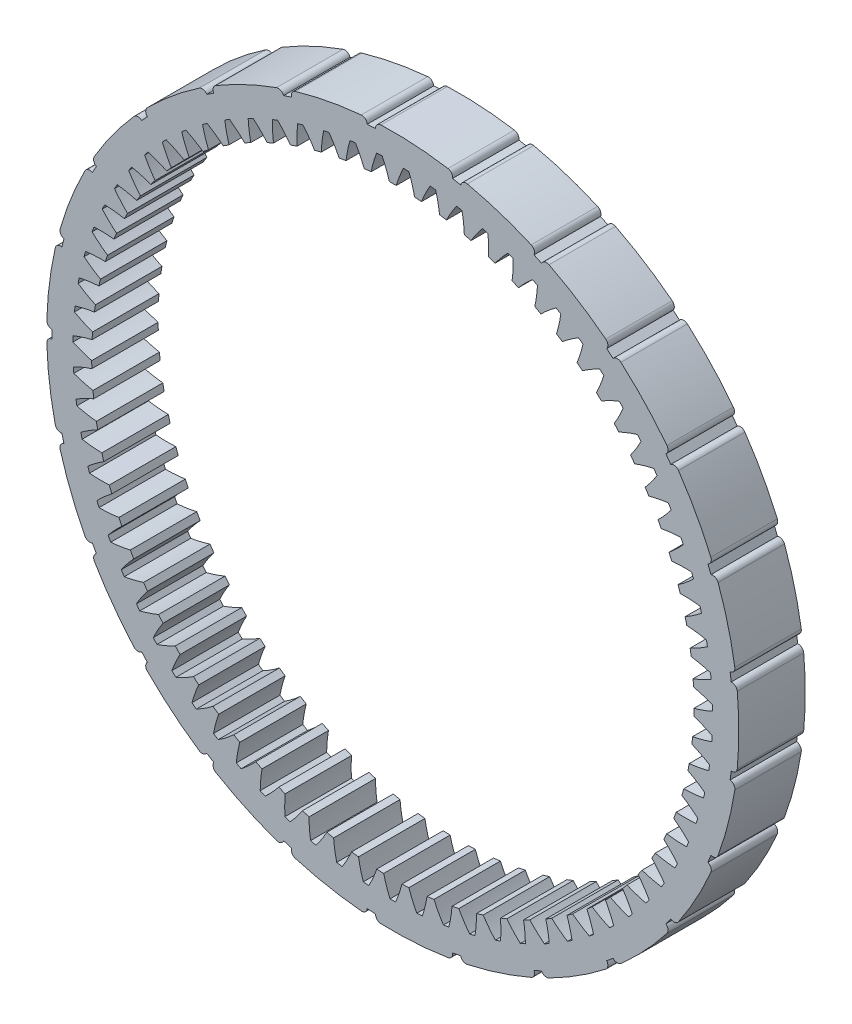
SolidWorks part; units mm, degrees
ref_plane "Front Plane" through (0, 0, 0) normal (0, 0, 1) x (1, 0, 0)
ref_plane "Top Plane" through (0, 0, 0) normal (0, 1, 0) x (1, 0, 0)
ref_plane "Right Plane" through (0, 0, 0) normal (1, 0, 0) x (0, 0, -1)
sketch "Sketch1" plane through (0, 0, 0) normal (0, 0, 1) x (1, 0, 0)
  arc A601 (-99.03, 33.1496) -> (-95.6559, 31.9283) centre (-89.7094, 53.6283) ccw
  arc A602 (-95.6559, 31.9283) -> (-95.6296, 30.6743) centre (-41.2843, 32.44) ccw
  arc A603 (-95.6296, 30.6743) -> (-98.9496, 29.3129) centre (-88.7797, 9.2424) ccw
  arc A604 (-98.9496, 29.3129) -> (-98.8868, 28.3151) centre (-41.2843, 32.44) ccw
  arc A605 (-98.8868, 28.3151) -> (-95.4224, 27.3804) centre (-91.3126, 49.5019) ccw
  arc A606 (-95.4224, 27.3804) -> (-95.2913, 26.133) centre (-41.2843, 32.44) ccw
  arc A607 (-95.2913, 26.133) -> (-98.4857, 24.4985) centre (-86.672, 5.3494) ccw
  arc A608 (-98.4857, 24.4985) -> (-98.3396, 23.5095) centre (-41.2843, 32.44) ccw
  arc A609 (-98.3396, 23.5095) -> (-94.8092, 22.868) centre (-92.5648, 45.2558) ccw
  arc A610 (-94.8092, 22.868) -> (-94.5741, 21.636) centre (-41.2843, 32.44) ccw
  arc A611 (-94.5741, 21.636) -> (-97.6205, 19.7399) centre (-84.2459, 1.6465) ccw
  arc A612 (-97.6205, 19.7399) -> (-97.3922, 18.7665) centre (-41.2843, 32.44) ccw
  arc A613 (-97.3922, 18.7665) -> (-93.8205, 18.4227) centre (-93.4574, 40.9198) ccw
  arc A614 (-93.8205, 18.4227) -> (-93.4832, 17.2147) centre (-41.2843, 32.44) ccw
  arc A615 (-93.4832, 17.2147) -> (-96.3602, 15.0703) centre (-81.5185, -1.8404) ccw
  arc A616 (-96.3602, 15.0703) -> (-96.0513, 14.1195) centre (-41.2843, 32.44) ccw
  arc A617 (-96.0513, 14.1195) -> (-92.4633, 14.0758) centre (-93.984, 36.5243) ccw
  arc A618 (-92.4633, 14.0758) -> (-92.0261, 12.9002) centre (-41.2843, 32.44) ccw
  arc A619 (-92.0261, 12.9002) -> (-94.7136, 10.5226) centre (-78.5089, -5.0869) ccw
  arc A620 (-94.7136, 10.5226) -> (-94.3262, 9.601) centre (-41.2843, 32.44) ccw
  arc A621 (-94.3262, 9.601) -> (-90.7471, 9.8576) centre (-94.1409, 32.1002) ccw
  arc A622 (-90.7471, 9.8576) -> (-90.2131, 8.7228) centre (-41.2843, 32.44) ccw
  arc A623 (-90.2131, 8.7228) -> (-92.6922, 6.1286) centre (-75.2382, -8.0702) ccw
  arc A624 (-92.6922, 6.1286) -> (-92.2291, 5.2426) centre (-41.2843, 32.44) ccw
  arc A625 (-92.2291, 5.2426) -> (-88.684, 5.7979) centre (-93.9271, 27.6785) ccw
  arc A626 (-88.684, 5.7979) -> (-88.0569, 4.7117) centre (-41.2843, 32.44) ccw
  arc A627 (-88.0569, 4.7117) -> (-90.3103, 1.9192) centre (-71.7293, -10.7693) ccw
  arc A628 (-90.3103, 1.9192) -> (-89.7746, 1.0751) centre (-41.2843, 32.44) ccw
  arc A629 (-89.7746, 1.0751) -> (-86.2884, 1.925) centre (-93.3441, 23.2901) ccw
  arc A630 (-86.2884, 1.925) -> (-85.5726, 0.8951) centre (-41.2843, 32.44) ccw
  arc A631 (-85.5726, 0.8951) -> (-87.5844, -2.0761) centre (-68.0069, -13.1653) ccw
  arc A632 (-87.5844, -2.0761) -> (-86.98, -2.8725) centre (-41.2843, 32.44) ccw
  arc A633 (-86.98, -2.8725) -> (-83.5772, -1.7338) centre (-92.3958, 18.966) ccw
  arc A634 (-83.5772, -1.7338) -> (-82.7777, -2.7002) centre (-41.2843, 32.44) ccw
  arc A635 (-82.7777, -2.7002) -> (-84.5338, -5.8294) centre (-64.097, -15.2415) ccw
  arc A636 (-84.5338, -5.8294) -> (-83.8648, -6.5724) centre (-41.2843, 32.44) ccw
  arc A637 (-83.8648, -6.5724) -> (-80.5692, -5.1529) centre (-91.0891, 14.7363) ccw
  arc A638 (-80.5692, -5.1529) -> (-79.6917, -6.0491) centre (-41.2843, 32.44) ccw
  arc A639 (-79.6917, -6.0491) -> (-81.1798, -9.3142) centre (-60.0271, -16.9832) ccw
  arc A640 (-81.1798, -9.3142) -> (-80.451, -9.9986) centre (-41.2843, 32.44) ccw
  arc A641 (-80.451, -9.9986) -> (-77.2858, -8.3084) centre (-89.433, 10.6308) ccw
  arc A642 (-77.2858, -8.3084) -> (-76.3363, -9.1279) centre (-41.2843, 32.44) ccw
  arc A643 (-76.3363, -9.1279) -> (-77.546, -12.5061) centre (-55.8258, -18.3782) ccw
  arc A644 (-77.546, -12.5061) -> (-76.7625, -13.1271) centre (-41.2843, 32.44) ccw
  arc A645 (-76.7625, -13.1271) -> (-73.7498, -11.178) centre (-87.4392, 6.6784) ccw
  arc A646 (-73.7498, -11.178) -> (-72.7351, -11.9152) centre (-41.2843, 32.44) ccw
  arc A647 (-72.7351, -11.9152) -> (-73.6578, -15.3828) centre (-51.5224, -19.4167) ccw
  arc A648 (-73.6578, -15.3828) -> (-72.8251, -15.9361) centre (-41.2843, 32.44) ccw
  arc A649 (-72.8251, -15.9361) -> (-69.9861, -13.7416) centre (-85.1217, 2.9066) ccw
  arc A650 (-69.9861, -13.7416) -> (-68.9132, -14.3914) centre (-41.2843, 32.44) ccw
  arc A651 (-68.9132, -14.3914) -> (-69.5426, -17.924) centre (-47.1472, -20.0916) ccw
  arc A652 (-69.5426, -17.924) -> (-68.6665, -18.4057) centre (-41.2843, 32.44) ccw
  arc A653 (-68.6665, -18.4057) -> (-66.021, -15.9814) centre (-82.4967, -0.6581) ccw
  arc A654 (-66.021, -15.9814) -> (-64.8976, -16.5391) centre (-41.2843, 32.44) ccw
  arc A655 (-64.8976, -16.5391) -> (-65.2291, -20.112) centre (-42.731, -20.3979) ccw
  arc A656 (-65.2291, -20.112) -> (-64.3158, -20.5186) centre (-41.2843, 32.44) ccw
  arc A657 (-64.3158, -20.5186) -> (-61.8825, -17.8815) centre (-79.5825, -3.9906) ccw
  arc A658 (-61.8825, -17.8815) -> (-60.7163, -18.3432) centre (-41.2843, 32.44) ccw
  arc A659 (-60.7163, -18.3432) -> (-60.7477, -21.9313) centre (-38.3045, -20.3337) ccw
  arc A660 (-60.7477, -21.9313) -> (-59.8036, -22.2601) centre (-41.2843, 32.44) ccw
  arc A661 (-59.8036, -22.2601) -> (-57.5994, -19.4286) centre (-76.3998, -7.0675) ccw
  arc A662 (-57.5994, -19.4286) -> (-56.3987, -19.7911) centre (-41.2843, 32.44) ccw
  arc A663 (-56.3987, -19.7911) -> (-56.1298, -23.3693) centre (-33.899, -19.8993) ccw
  arc A664 (-56.1298, -23.3693) -> (-55.1614, -23.6179) centre (-41.2843, 32.44) ccw
  arc A665 (-55.1614, -23.6179) -> (-53.202, -20.6119) centre (-72.9707, -9.8673) ccw
  arc A666 (-53.202, -20.6119) -> (-51.9751, -20.8727) centre (-41.2843, 32.44) ccw
  arc A667 (-51.9751, -20.8727) -> (-51.4077, -24.4158) centre (-29.5453, -19.0977) ccw
  arc A668 (-51.4077, -24.4158) -> (-50.422, -24.5825) centre (-41.2843, 32.44) ccw
  arc A669 (-50.422, -24.5825) -> (-48.7209, -21.4231) centre (-69.3194, -12.3704) ccw
  arc A670 (-48.7209, -21.4231) -> (-47.4766, -21.5803) centre (-41.2843, 32.44) ccw
  arc A671 (-47.4766, -21.5803) -> (-46.6147, -25.0635) centre (-25.2739, -17.9347) ccw
  arc A672 (-46.6147, -25.0635) -> (-45.6184, -25.1472) centre (-41.2843, 32.44) ccw
  arc A673 (-45.6184, -25.1472) -> (-44.1877, -21.8565) centre (-65.4715, -14.5592) ccw
  arc A674 (-44.1877, -21.8565) -> (-42.9345, -21.909) centre (-41.2843, 32.44) ccw
  arc A675 (-42.9345, -21.909) -> (-41.7842, -25.3079) centre (-21.1148, -16.4183) ccw
  arc A676 (-41.7842, -25.3079) -> (-40.7844, -25.3079) centre (-41.2843, 32.44) ccw
  arc A677 (-40.7844, -25.3079) -> (-39.6341, -21.909) centre (-61.4539, -16.4183) ccw
  arc A678 (-39.6341, -21.909) -> (-38.3809, -21.8565) centre (-41.2843, 32.44) ccw
  arc A679 (-38.3809, -21.8565) -> (-36.9502, -25.1472) centre (-17.0972, -14.5592) ccw
  arc A680 (-36.9502, -25.1472) -> (-35.954, -25.0635) centre (-41.2843, 32.44) ccw
  arc A681 (-35.954, -25.0635) -> (-35.0921, -21.5803) centre (-57.2948, -17.9347) ccw
  arc A682 (-35.0921, -21.5803) -> (-33.8477, -21.4231) centre (-41.2843, 32.44) ccw
  arc A683 (-33.8477, -21.4231) -> (-32.1467, -24.5825) centre (-13.2492, -12.3704) ccw
  arc A684 (-32.1467, -24.5825) -> (-31.1609, -24.4158) centre (-41.2843, 32.44) ccw
  arc A685 (-31.1609, -24.4158) -> (-30.5935, -20.8727) centre (-53.0234, -19.0977) ccw
  arc A686 (-30.5935, -20.8727) -> (-29.3667, -20.6119) centre (-41.2843, 32.44) ccw
  arc A687 (-29.3667, -20.6119) -> (-27.4072, -23.6179) centre (-9.5979, -9.8673) ccw
  arc A688 (-27.4072, -23.6179) -> (-26.4388, -23.3693) centre (-41.2843, 32.44) ccw
  arc A689 (-26.4388, -23.3693) -> (-26.1699, -19.7911) centre (-48.6696, -19.8993) ccw
  arc A690 (-26.1699, -19.7911) -> (-24.9692, -19.4286) centre (-41.2843, 32.44) ccw
  arc A691 (-24.9692, -19.4286) -> (-22.7651, -22.2601) centre (-6.1688, -7.0675) ccw
  arc A692 (-22.7651, -22.2601) -> (-21.8209, -21.9313) centre (-41.2843, 32.44) ccw
  arc A693 (-21.8209, -21.9313) -> (-21.8523, -18.3432) centre (-44.2641, -20.3337) ccw
  arc A694 (-21.8523, -18.3432) -> (-20.6862, -17.8815) centre (-41.2843, 32.44) ccw
  arc A695 (-20.6862, -17.8815) -> (-18.2528, -20.5186) centre (-2.9861, -3.9906) ccw
  arc A696 (-18.2528, -20.5186) -> (-17.3395, -20.112) centre (-41.2843, 32.44) ccw
  arc A697 (-17.3395, -20.112) -> (-17.6711, -16.5391) centre (-39.8377, -20.3979) ccw
  arc A698 (-17.6711, -16.5391) -> (-16.5476, -15.9814) centre (-41.2843, 32.44) ccw
  arc A699 (-16.5476, -15.9814) -> (-13.9021, -18.4057) centre (-0.072, -0.6581) ccw
  arc A700 (-13.9021, -18.4057) -> (-13.026, -17.924) centre (-41.2843, 32.44) ccw
  arc A701 (-13.026, -17.924) -> (-13.6554, -14.3914) centre (-35.4214, -20.0916) ccw
  arc A702 (-13.6554, -14.3914) -> (-12.5826, -13.7416) centre (-41.2843, 32.44) ccw
  arc A703 (-12.5826, -13.7416) -> (-9.7435, -15.9361) centre (2.5531, 2.9066) ccw
  arc A704 (-9.7435, -15.9361) -> (-8.9108, -15.3828) centre (-41.2843, 32.44) ccw
  arc A705 (-8.9108, -15.3828) -> (-9.8336, -11.9152) centre (-31.0462, -19.4167) ccw
  arc A706 (-9.8336, -11.9152) -> (-8.8189, -11.178) centre (-41.2843, 32.44) ccw
  arc A707 (-8.8189, -11.178) -> (-5.8061, -13.1271) centre (4.8706, 6.6784) ccw
  arc A708 (-5.8061, -13.1271) -> (-5.0226, -12.5061) centre (-41.2843, 32.44) ccw
  arc A709 (-5.0226, -12.5061) -> (-6.2323, -9.1279) centre (-26.7429, -18.3782) ccw
  arc A710 (-6.2323, -9.1279) -> (-5.2829, -8.3084) centre (-41.2843, 32.44) ccw
  arc A711 (-5.2829, -8.3084) -> (-2.1176, -9.9986) centre (6.8644, 10.6308) ccw
  arc A712 (-2.1176, -9.9986) -> (-1.3888, -9.3142) centre (-41.2843, 32.44) ccw
  arc A713 (-1.3888, -9.3142) -> (-2.8769, -6.0491) centre (-22.5415, -16.9832) ccw
  arc A714 (-2.8769, -6.0491) -> (-1.9994, -5.1529) centre (-41.2843, 32.44) ccw
  arc A715 (-1.9994, -5.1529) -> (1.2962, -6.5724) centre (8.5205, 14.7363) ccw
  arc A716 (1.2962, -6.5724) -> (1.9652, -5.8294) centre (-41.2843, 32.44) ccw
  arc A717 (1.9652, -5.8294) -> (0.209, -2.7002) centre (-18.4716, -15.2415) ccw
  arc A718 (0.209, -2.7002) -> (1.0085, -1.7338) centre (-41.2843, 32.44) ccw
  arc A719 (1.0085, -1.7338) -> (4.4113, -2.8725) centre (9.8272, 18.966) ccw
  arc A720 (4.4113, -2.8725) -> (5.0158, -2.0761) centre (-41.2843, 32.44) ccw
  arc A721 (5.0158, -2.0761) -> (3.004, 0.8951) centre (-14.5618, -13.1653) ccw
  arc A722 (3.004, 0.8951) -> (3.7198, 1.925) centre (-41.2843, 32.44) ccw
  arc A723 (3.7198, 1.925) -> (7.2059, 1.0751) centre (10.7754, 23.2901) ccw
  arc A724 (7.2059, 1.0751) -> (7.7416, 1.9192) centre (-41.2843, 32.44) ccw
  arc A725 (7.7416, 1.9192) -> (5.4883, 4.7117) centre (-10.8393, -10.7693) ccw
  arc A726 (5.4883, 4.7117) -> (6.1154, 5.7979) centre (-41.2843, 32.44) ccw
  arc A727 (6.1154, 5.7979) -> (9.6604, 5.2426) centre (11.3585, 27.6785) ccw
  arc A728 (9.6604, 5.2426) -> (10.1236, 6.1286) centre (-41.2843, 32.44) ccw
  arc A729 (10.1236, 6.1286) -> (7.6445, 8.7228) centre (-7.3304, -8.0702) ccw
  arc A730 (7.6445, 8.7228) -> (8.1785, 9.8576) centre (-41.2843, 32.44) ccw
  arc A731 (8.1785, 9.8576) -> (11.7576, 9.601) centre (11.5723, 32.1002) ccw
  arc A732 (11.7576, 9.601) -> (12.145, 10.5226) centre (-41.2843, 32.44) ccw
  arc A733 (12.145, 10.5226) -> (9.4575, 12.9002) centre (-4.0597, -5.0869) ccw
  arc A734 (9.4575, 12.9002) -> (9.8947, 14.0758) centre (-41.2843, 32.44) ccw
  arc A735 (9.8947, 14.0758) -> (13.4827, 14.1195) centre (11.4154, 36.5243) ccw
  arc A736 (13.4827, 14.1195) -> (13.7916, 15.0703) centre (-41.2843, 32.44) ccw
  arc A737 (13.7916, 15.0703) -> (10.9146, 17.2147) centre (-1.0501, -1.8404) ccw
  arc A738 (10.9146, 17.2147) -> (11.2518, 18.4227) centre (-41.2843, 32.44) ccw
  arc A739 (11.2518, 18.4227) -> (14.8236, 18.7665) centre (10.8888, 40.9198) ccw
  arc A740 (14.8236, 18.7665) -> (15.0519, 19.7399) centre (-41.2843, 32.44) ccw
  arc A741 (15.0519, 19.7399) -> (12.0055, 21.636) centre (1.6773, 1.6465) ccw
  arc A742 (12.0055, 21.636) -> (12.2405, 22.868) centre (-41.2843, 32.44) ccw
  arc A743 (12.2405, 22.868) -> (15.771, 23.5095) centre (9.9962, 45.2558) ccw
  arc A744 (15.771, 23.5095) -> (15.917, 24.4985) centre (-41.2843, 32.44) ccw
  arc A745 (15.917, 24.4985) -> (12.7227, 26.133) centre (4.1034, 5.3494) ccw
  arc A746 (12.7227, 26.133) -> (12.8538, 27.3804) centre (-41.2843, 32.44) ccw
  arc A747 (12.8538, 27.3804) -> (16.3182, 28.3151) centre (8.744, 49.5019) ccw
  arc A748 (16.3182, 28.3151) -> (16.381, 29.3129) centre (-41.2843, 32.44) ccw
  arc A749 (16.381, 29.3129) -> (13.061, 30.6743) centre (6.2111, 9.2424) ccw
  arc A750 (13.061, 30.6743) -> (13.0873, 31.9283) centre (-41.2843, 32.44) ccw
  arc A751 (13.0873, 31.9283) -> (16.4613, 33.1496) centre (7.1408, 53.6283) ccw
  arc A752 (16.4613, 33.1496) -> (16.4404, 34.1491) centre (-41.2843, 32.44) ccw
  arc A753 (16.4404, 34.1491) -> (13.0182, 35.228) centre (7.9856, 13.2981) ccw
  arc A754 (13.0182, 35.228) -> (12.9394, 36.4798) centre (-41.2843, 32.44) ccw
  arc A755 (12.9394, 36.4798) -> (16.1994, 37.9791) centre (5.198, 57.6061) ccw
  arc A756 (16.1994, 37.9791) -> (16.0949, 38.9734) centre (-41.2843, 32.44) ccw
  arc A757 (16.0949, 38.9734) -> (12.5944, 39.7622) centre (9.4146, 17.488) ccw
  arc A758 (12.5944, 39.7622) -> (12.4112, 41.003) centre (-41.2843, 32.44) ccw
  arc A759 (12.4112, 41.003) -> (15.5343, 42.7698) centre (2.9291, 61.4074) ccw
  arc A760 (15.5343, 42.7698) -> (15.347, 43.7519) centre (-41.2843, 32.44) ccw
  arc A761 (15.347, 43.7519) -> (11.7927, 44.2449) centre (10.4879, 21.7828) ccw
  arc A762 (11.7927, 44.2449) -> (11.5063, 45.466) centre (-41.2843, 32.44) ccw
  arc A763 (11.5063, 45.466) -> (14.4707, 47.488) centre (0.3501, 65.0055) ccw
  arc A764 (14.4707, 47.488) -> (14.2018, 48.451) centre (-41.2843, 32.44) ccw
  arc A765 (14.2018, 48.451) -> (10.6188, 48.6449) centre (11.1981, 26.1524) ccw
  arc A766 (10.6188, 48.6449) -> (10.2312, 49.8378) centre (-41.2843, 32.44) ccw
  arc A767 (10.2312, 49.8378) -> (13.0159, 52.1007) centre (-2.5209, 68.3751) ccw
  arc A768 (13.0159, 52.1007) -> (12.6674, 53.0378) centre (-41.2843, 32.44) ccw
  arc A769 (12.6674, 53.0378) -> (9.0808, 52.9312) centre (11.5402, 30.566) ccw
  arc A770 (9.0808, 52.9312) -> (8.5947, 54.0875) centre (-41.2843, 32.44) ccw
  arc A771 (8.5947, 54.0875) -> (11.1803, 56.5755) centre (-5.6638, 71.4927) ccw
  arc A772 (11.1803, 56.5755) -> (10.7546, 57.4801) centre (-41.2843, 32.44) ccw
  arc A773 (10.7546, 57.4801) -> (7.1895, 57.0738) centre (11.5117, 34.9929) ccw
  arc A774 (7.1895, 57.0738) -> (6.6084, 58.1853) centre (-41.2843, 32.44) ccw
  arc A775 (6.6084, 58.1853) -> (8.9767, 60.881) centre (-9.0566, 74.3364) ccw
  arc A776 (8.9767, 60.881) -> (8.4768, 61.7468) centre (-41.2843, 32.44) ccw
  arc A777 (8.4768, 61.7468) -> (4.9581, 61.0436) centre (11.1129, 39.4018) ccw
  arc A778 (4.9581, 61.0436) -> (4.2861, 62.1026) centre (-41.2843, 32.44) ccw
  arc A779 (4.2861, 62.1026) -> (6.4206, 64.987) centre (-12.6754, 76.8862) ccw
  arc A780 (6.4206, 64.987) -> (5.85, 65.8079) centre (-41.2843, 32.44) ccw
  arc A781 (5.85, 65.8079) -> (2.4025, 64.8127) centre (10.3466, 43.7618) ccw
  arc A782 (2.4025, 64.8127) -> (1.6442, 65.8118) centre (-41.2843, 32.44) ccw
  arc A783 (1.6442, 65.8118) -> (3.5298, 68.8647) centre (-16.4949, 79.1243) ccw
  arc A784 (3.5298, 68.8647) -> (2.8925, 69.635) centre (-41.2843, 32.44) ccw
  arc A785 (2.8925, 69.635) -> (-0.4596, 68.3548) centre (9.2181, 48.0425) ccw
  arc A786 (-0.4596, 68.3548) -> (-1.2989, 69.2869) centre (-41.2843, 32.44) ccw
  arc A787 (-1.2989, 69.2869) -> (0.3247, 72.4869) centre (-20.4883, 81.0349) ccw
  arc A788 (0.3247, 72.4869) -> (-0.3748, 73.2012) centre (-41.2843, 32.44) ccw
  arc A789 (-0.3748, 73.2012) -> (-3.6081, 71.645) centre (7.7354, 52.2137) ccw
  arc A790 (-3.6081, 71.645) -> (-4.5224, 72.5036) centre (-41.2843, 32.44) ccw
  arc A791 (-4.5224, 72.5036) -> (-3.1723, 75.8282) centre (-24.6276, 82.6046) ccw
  arc A792 (-3.1723, 75.8282) -> (-3.9291, 76.4814) centre (-41.2843, 32.44) ccw
  arc A793 (-3.9291, 76.4814) -> (-7.0208, 74.6601) centre (5.9089, 56.2462) ccw
  arc A794 (-7.0208, 74.6601) -> (-8.0037, 75.4392) centre (-41.2843, 32.44) ccw
  arc A795 (-8.0037, 75.4392) -> (-6.9366, 78.8651) centre (-28.8837, 83.8225) ccw
  arc A796 (-6.9366, 78.8651) -> (-7.7454, 79.4528) centre (-41.2843, 32.44) ccw
  arc A797 (-7.7454, 79.4528) -> (-10.6739, 77.3792) centre (3.7513, 60.1118) ccw
  arc A798 (-10.6739, 77.3792) -> (-11.7185, 78.0733) centre (-41.2843, 32.44) ccw
  arc A799 (-11.7185, 78.0733) -> (-10.9418, 81.5765) centre (-33.2267, 84.6799) ccw
  arc A800 (-10.9418, 81.5765) -> (-11.797, 82.0944) centre (-41.2843, 32.44) ccw
  arc A801 (-11.797, 82.0944) -> (-14.5416, 79.783) centre (1.2779, 63.7832) ccw
  arc A802 (-14.5416, 79.783) -> (-15.6407, 80.3872) centre (-41.2843, 32.44) ccw
  arc A803 (-15.6407, 80.3872) -> (-15.1598, 83.9431) centre (-37.6263, 85.171) ccw
  arc A804 (-15.1598, 83.9431) -> (-16.0553, 84.3877) centre (-41.2843, 32.44) ccw
  arc A805 (-16.0553, 84.3877) -> (-18.597, 81.8547) centre (-1.4941, 67.2348) ccw
  arc A806 (-18.597, 81.8547) -> (-19.7428, 82.3649) centre (-41.2843, 32.44) ccw
  arc A807 (-19.7428, 82.3649) -> (-19.5611, 85.9485) centre (-42.0516, 85.2921) ccw
  arc A808 (-19.5611, 85.9485) -> (-20.4907, 86.3166) centre (-41.2843, 32.44) ccw
  arc A809 (-20.4907, 86.3166) -> (-22.8115, 83.5798) centre (-4.5452, 70.4423) ccw
  arc A810 (-22.8115, 83.5798) -> (-23.9959, 83.9923) centre (-41.2843, 32.44) ccw
  arc A811 (-23.9959, 83.9923) -> (-24.1148, 87.5786) centre (-46.4714, 85.0425) ccw
  arc A812 (-24.1148, 87.5786) -> (-25.0719, 87.8676) centre (-41.2843, 32.44) ccw
  arc A813 (-25.0719, 87.8676) -> (-27.1555, 84.9462) centre (-7.854, 73.3833) ccw
  arc A814 (-27.1555, 84.9462) -> (-28.3704, 85.2582) centre (-41.2843, 32.44) ccw
  arc A815 (-28.3704, 85.2582) -> (-28.7889, 88.8219) centre (-50.8549, 84.424) ccw
  arc A816 (-28.7889, 88.8219) -> (-29.7668, 89.0298) centre (-41.2843, 32.44) ccw
  arc A817 (-29.7668, 89.0298) -> (-31.5987, 85.9444) centre (-11.3973, 76.0371) ccw
  arc A818 (-31.5987, 85.9444) -> (-32.8354, 86.1535) centre (-41.2843, 32.44) ccw
  arc A819 (-32.8354, 86.1535) -> (-33.5507, 89.6698) centre (-55.1713, 83.4409) ccw
  arc A820 (-33.5507, 89.6698) -> (-34.5425, 89.7951) centre (-41.2843, 32.44) ccw
  arc A821 (-34.5425, 89.7951) -> (-36.1098, 86.5672) centre (-15.1503, 78.385) ccw
  arc A822 (-36.1098, 86.5672) -> (-37.3596, 86.6721) centre (-41.2843, 32.44) ccw
  arc A823 (-37.3596, 86.6721) -> (-38.3666, 90.1162) centre (-59.3902, 82.1) ccw
  arc A824 (-38.3666, 90.1162) -> (-39.3655, 90.1581) centre (-41.2843, 32.44) ccw
  arc A825 (-39.3655, 90.1581) -> (-40.6572, 86.8104) centre (-19.0865, 80.4107) ccw
  arc A826 (-40.6572, 86.8104) -> (-41.9114, 86.8104) centre (-41.2843, 32.44) ccw
  arc A827 (-41.9114, 86.8104) -> (-43.2031, 90.1581) centre (-63.4821, 80.4107) ccw
  arc A828 (-43.2031, 90.1581) -> (-44.202, 90.1162) centre (-41.2843, 32.44) ccw
  arc A829 (-44.202, 90.1162) -> (-45.209, 86.6721) centre (-23.1784, 82.1) ccw
  arc A830 (-45.209, 86.6721) -> (-46.4588, 86.5672) centre (-41.2843, 32.44) ccw
  arc A831 (-46.4588, 86.5672) -> (-48.0261, 89.7951) centre (-67.4184, 78.385) ccw
  arc A832 (-48.0261, 89.7951) -> (-49.018, 89.6698) centre (-41.2843, 32.44) ccw
  arc A833 (-49.018, 89.6698) -> (-49.7333, 86.1535) centre (-27.3974, 83.4409) ccw
  arc A834 (-49.7333, 86.1535) -> (-50.9699, 85.9444) centre (-41.2843, 32.44) ccw
  arc A835 (-50.9699, 85.9444) -> (-52.8018, 89.0298) centre (-71.1713, 76.0371) ccw
  arc A836 (-52.8018, 89.0298) -> (-53.7797, 88.8219) centre (-41.2843, 32.44) ccw
  arc A837 (-53.7797, 88.8219) -> (-54.1983, 85.2582) centre (-31.7137, 84.424) ccw
  arc A838 (-54.1983, 85.2582) -> (-55.4131, 84.9462) centre (-41.2843, 32.44) ccw
  arc A839 (-55.4131, 84.9462) -> (-57.4967, 87.8676) centre (-74.7146, 73.3833) ccw
  arc A840 (-57.4967, 87.8676) -> (-58.4538, 87.5786) centre (-41.2843, 32.44) ccw
  arc A841 (-58.4538, 87.5786) -> (-58.5727, 83.9923) centre (-36.0972, 85.0425) ccw
  arc A842 (-58.5727, 83.9923) -> (-59.7572, 83.5798) centre (-41.2843, 32.44) ccw
  arc A843 (-59.7572, 83.5798) -> (-62.0779, 86.3166) centre (-78.0234, 70.4423) ccw
  arc A844 (-62.0779, 86.3166) -> (-63.0075, 85.9485) centre (-41.2843, 32.44) ccw
  arc A845 (-63.0075, 85.9485) -> (-62.8258, 82.3649) centre (-40.5171, 85.2921) ccw
  arc A846 (-62.8258, 82.3649) -> (-63.9716, 81.8547) centre (-41.2843, 32.44) ccw
  arc A847 (-63.9716, 81.8547) -> (-66.5133, 84.3877) centre (-81.0745, 67.2348) ccw
  arc A848 (-66.5133, 84.3877) -> (-67.4088, 83.9431) centre (-41.2843, 32.44) ccw
  arc A849 (-67.4088, 83.9431) -> (-66.9279, 80.3872) centre (-44.9423, 85.171) ccw
  arc A850 (-66.9279, 80.3872) -> (-68.027, 79.783) centre (-41.2843, 32.44) ccw
  arc A851 (-68.027, 79.783) -> (-70.7717, 82.0944) centre (-83.8465, 63.7832) ccw
  arc A852 (-70.7717, 82.0944) -> (-71.6268, 81.5765) centre (-41.2843, 32.44) ccw
  arc A853 (-71.6268, 81.5765) -> (-70.8501, 78.0733) centre (-49.3419, 84.6799) ccw
  arc A854 (-70.8501, 78.0733) -> (-71.8948, 77.3792) centre (-41.2843, 32.44) ccw
  arc A855 (-71.8948, 77.3792) -> (-74.8232, 79.4528) centre (-86.32, 60.1118) ccw
  arc A856 (-74.8232, 79.4528) -> (-75.6321, 78.8651) centre (-41.2843, 32.44) ccw
  arc A857 (-75.6321, 78.8651) -> (-74.5649, 75.4392) centre (-53.685, 83.8225) ccw
  arc A858 (-74.5649, 75.4392) -> (-75.5478, 74.6601) centre (-41.2843, 32.44) ccw
  arc A859 (-75.5478, 74.6601) -> (-78.6395, 76.4814) centre (-88.4775, 56.2462) ccw
  arc A860 (-78.6395, 76.4814) -> (-79.3964, 75.8282) centre (-41.2843, 32.44) ccw
  arc A861 (-79.3964, 75.8282) -> (-78.0463, 72.5036) centre (-57.9411, 82.6046) ccw
  arc A862 (-78.0463, 72.5036) -> (-78.9606, 71.645) centre (-41.2843, 32.44) ccw
  arc A863 (-78.9606, 71.645) -> (-82.1938, 73.2012) centre (-90.3041, 52.2137) ccw
  arc A864 (-82.1938, 73.2012) -> (-82.8933, 72.4869) centre (-41.2843, 32.44) ccw
  arc A865 (-82.8933, 72.4869) -> (-81.2698, 69.2869) centre (-62.0803, 81.0349) ccw
  arc A866 (-81.2698, 69.2869) -> (-82.109, 68.3548) centre (-41.2843, 32.44) ccw
  arc A867 (-82.109, 68.3548) -> (-85.4612, 69.635) centre (-91.7868, 48.0425) ccw
  arc A868 (-85.4612, 69.635) -> (-86.0984, 68.8647) centre (-41.2843, 32.44) ccw
  arc A869 (-86.0984, 68.8647) -> (-84.2128, 65.8118) centre (-66.0737, 79.1243) ccw
  arc A870 (-84.2128, 65.8118) -> (-84.9711, 64.8127) centre (-41.2843, 32.44) ccw
  arc A871 (-84.9711, 64.8127) -> (-88.4186, 65.8079) centre (-92.9152, 43.7618) ccw
  arc A872 (-88.4186, 65.8079) -> (-88.9892, 64.987) centre (-41.2843, 32.44) ccw
  arc A873 (-88.9892, 64.987) -> (-86.8547, 62.1026) centre (-69.8932, 76.8862) ccw
  arc A874 (-86.8547, 62.1026) -> (-87.5268, 61.0436) centre (-41.2843, 32.44) ccw
  arc A875 (-87.5268, 61.0436) -> (-91.0455, 61.7468) centre (-93.6816, 39.4018) ccw
  arc A876 (-91.0455, 61.7468) -> (-91.5454, 60.881) centre (-41.2843, 32.44) ccw
  arc A877 (-91.5454, 60.881) -> (-89.177, 58.1853) centre (-73.512, 74.3364) ccw
  arc A878 (-89.177, 58.1853) -> (-89.7581, 57.0738) centre (-41.2843, 32.44) ccw
  arc A879 (-89.7581, 57.0738) -> (-93.3233, 57.4801) centre (-94.0803, 34.9929) ccw
  arc A880 (-93.3233, 57.4801) -> (-93.749, 56.5755) centre (-41.2843, 32.44) ccw
  arc A881 (-93.749, 56.5755) -> (-91.1633, 54.0875) centre (-76.9048, 71.4927) ccw
  arc A882 (-91.1633, 54.0875) -> (-91.6494, 52.9312) centre (-41.2843, 32.44) ccw
  arc A883 (-91.6494, 52.9312) -> (-95.2361, 53.0378) centre (-94.1088, 30.566) ccw
  arc A884 (-95.2361, 53.0378) -> (-95.5846, 52.1007) centre (-41.2843, 32.44) ccw
  arc A885 (-95.5846, 52.1007) -> (-92.7998, 49.8378) centre (-80.0477, 68.3751) ccw
  arc A886 (-92.7998, 49.8378) -> (-93.1874, 48.6449) centre (-41.2843, 32.44) ccw
  arc A887 (-93.1874, 48.6449) -> (-96.7704, 48.451) centre (-93.7667, 26.1524) ccw
  arc A888 (-96.7704, 48.451) -> (-97.0393, 47.488) centre (-41.2843, 32.44) ccw
  arc A889 (-97.0393, 47.488) -> (-94.075, 45.466) centre (-82.9188, 65.0055) ccw
  arc A890 (-94.075, 45.466) -> (-94.3614, 44.2449) centre (-41.2843, 32.44) ccw
  arc A891 (-94.3614, 44.2449) -> (-97.9156, 43.7519) centre (-93.0565, 21.7828) ccw
  arc A892 (-97.9156, 43.7519) -> (-98.1029, 42.7698) centre (-41.2843, 32.44) ccw
  arc A893 (-98.1029, 42.7698) -> (-94.9798, 41.003) centre (-85.4977, 61.4074) ccw
  arc A894 (-94.9798, 41.003) -> (-95.163, 39.7622) centre (-41.2843, 32.44) ccw
  arc A895 (-95.163, 39.7622) -> (-98.6636, 38.9734) centre (-91.9832, 17.488) ccw
  arc A896 (-98.6636, 38.9734) -> (-98.7681, 37.9791) centre (-41.2843, 32.44) ccw
  arc A897 (-98.7681, 37.9791) -> (-95.508, 36.4798) centre (-87.7666, 57.6061) ccw
  arc A898 (-95.508, 36.4798) -> (-95.5868, 35.228) centre (-41.2843, 32.44) ccw
  arc A899 (-95.5868, 35.228) -> (-99.009, 34.1491) centre (-90.5542, 13.2981) ccw
  arc A900 (-99.009, 34.1491) -> (-99.03, 33.1496) centre (-41.2843, 32.44) ccw
sketch "Sketch2" plane through (0, 0, 0) normal (0, 0, 1) x (1, 0, 0)
  circle A0 centre (-41.2843, 32.44) radius 62.5
  arc A300 (-30.5935, -20.8727) -> (-29.3667, -20.6119) centre (-41.2843, 32.44) ccw
  arc A301 (-29.3667, -20.6119) -> (-27.4072, -23.6179) centre (-9.5979, -9.8673) ccw
  arc A302 (-27.4072, -23.6179) -> (-26.4388, -23.3693) centre (-41.2843, 32.44) ccw
  arc A303 (-26.4388, -23.3693) -> (-26.1699, -19.7911) centre (-48.6696, -19.8993) ccw
  arc A304 (-26.1699, -19.7911) -> (-24.9692, -19.4286) centre (-41.2843, 32.44) ccw
  arc A305 (-24.9692, -19.4286) -> (-22.7651, -22.2601) centre (-6.1688, -7.0675) ccw
  arc A306 (-22.7651, -22.2601) -> (-21.8209, -21.9313) centre (-41.2843, 32.44) ccw
  arc A307 (-21.8209, -21.9313) -> (-21.8523, -18.3432) centre (-44.2641, -20.3337) ccw
  arc A308 (-21.8523, -18.3432) -> (-20.6862, -17.8815) centre (-41.2843, 32.44) ccw
  arc A309 (-20.6862, -17.8815) -> (-18.2528, -20.5186) centre (-2.9861, -3.9906) ccw
  arc A310 (-18.2528, -20.5186) -> (-17.3395, -20.112) centre (-41.2843, 32.44) ccw
  arc A311 (-17.3395, -20.112) -> (-17.6711, -16.5391) centre (-39.8377, -20.3979) ccw
  arc A312 (-17.6711, -16.5391) -> (-16.5476, -15.9814) centre (-41.2843, 32.44) ccw
  arc A313 (-16.5476, -15.9814) -> (-13.9021, -18.4057) centre (-0.072, -0.6581) ccw
  arc A314 (-13.9021, -18.4057) -> (-13.026, -17.924) centre (-41.2843, 32.44) ccw
  arc A315 (-13.026, -17.924) -> (-13.6554, -14.3914) centre (-35.4214, -20.0916) ccw
  arc A316 (-13.6554, -14.3914) -> (-12.5826, -13.7416) centre (-41.2843, 32.44) ccw
  arc A317 (-12.5826, -13.7416) -> (-9.7435, -15.9361) centre (2.5531, 2.9066) ccw
  arc A318 (-9.7435, -15.9361) -> (-8.9108, -15.3828) centre (-41.2843, 32.44) ccw
  arc A319 (-8.9108, -15.3828) -> (-9.8336, -11.9152) centre (-31.0462, -19.4167) ccw
  arc A320 (-9.8336, -11.9152) -> (-8.8189, -11.178) centre (-41.2843, 32.44) ccw
  arc A321 (-8.8189, -11.178) -> (-5.8061, -13.1271) centre (4.8706, 6.6784) ccw
  arc A322 (-5.8061, -13.1271) -> (-5.0226, -12.5061) centre (-41.2843, 32.44) ccw
  arc A323 (-5.0226, -12.5061) -> (-6.2323, -9.1279) centre (-26.7429, -18.3782) ccw
  arc A324 (-6.2323, -9.1279) -> (-5.2829, -8.3084) centre (-41.2843, 32.44) ccw
  arc A325 (-5.2829, -8.3084) -> (-2.1176, -9.9986) centre (6.8644, 10.6308) ccw
  arc A326 (-2.1176, -9.9986) -> (-1.3888, -9.3142) centre (-41.2843, 32.44) ccw
  arc A327 (-1.3888, -9.3142) -> (-2.8769, -6.0491) centre (-22.5415, -16.9832) ccw
  arc A328 (-2.8769, -6.0491) -> (-1.9994, -5.1529) centre (-41.2843, 32.44) ccw
  arc A329 (-1.9994, -5.1529) -> (1.2962, -6.5724) centre (8.5205, 14.7363) ccw
  arc A330 (1.2962, -6.5724) -> (1.9652, -5.8294) centre (-41.2843, 32.44) ccw
  arc A331 (1.9652, -5.8294) -> (0.209, -2.7002) centre (-18.4716, -15.2415) ccw
  arc A332 (0.209, -2.7002) -> (1.0085, -1.7338) centre (-41.2843, 32.44) ccw
  arc A333 (1.0085, -1.7338) -> (4.4113, -2.8725) centre (9.8272, 18.966) ccw
  arc A334 (4.4113, -2.8725) -> (5.0158, -2.0761) centre (-41.2843, 32.44) ccw
  arc A335 (5.0158, -2.0761) -> (3.004, 0.8951) centre (-14.5618, -13.1653) ccw
  arc A336 (3.004, 0.8951) -> (3.7198, 1.925) centre (-41.2843, 32.44) ccw
  arc A337 (3.7198, 1.925) -> (7.2059, 1.0751) centre (10.7754, 23.2901) ccw
  arc A338 (7.2059, 1.0751) -> (7.7416, 1.9192) centre (-41.2843, 32.44) ccw
  arc A339 (7.7416, 1.9192) -> (5.4883, 4.7117) centre (-10.8393, -10.7693) ccw
  arc A340 (5.4883, 4.7117) -> (6.1154, 5.7979) centre (-41.2843, 32.44) ccw
  arc A341 (6.1154, 5.7979) -> (9.6604, 5.2426) centre (11.3585, 27.6785) ccw
  arc A342 (9.6604, 5.2426) -> (10.1236, 6.1286) centre (-41.2843, 32.44) ccw
  arc A343 (10.1236, 6.1286) -> (7.6445, 8.7228) centre (-7.3304, -8.0702) ccw
  arc A344 (7.6445, 8.7228) -> (8.1785, 9.8576) centre (-41.2843, 32.44) ccw
  arc A345 (8.1785, 9.8576) -> (11.7576, 9.601) centre (11.5723, 32.1002) ccw
  arc A346 (11.7576, 9.601) -> (12.145, 10.5226) centre (-41.2843, 32.44) ccw
  arc A347 (12.145, 10.5226) -> (9.4575, 12.9002) centre (-4.0597, -5.0869) ccw
  arc A348 (9.4575, 12.9002) -> (9.8947, 14.0758) centre (-41.2843, 32.44) ccw
  arc A349 (9.8947, 14.0758) -> (13.4827, 14.1195) centre (11.4154, 36.5243) ccw
  arc A350 (13.4827, 14.1195) -> (13.7916, 15.0703) centre (-41.2843, 32.44) ccw
  arc A351 (13.7916, 15.0703) -> (10.9146, 17.2147) centre (-1.0501, -1.8404) ccw
  arc A352 (10.9146, 17.2147) -> (11.2518, 18.4227) centre (-41.2843, 32.44) ccw
  arc A353 (11.2518, 18.4227) -> (14.8236, 18.7665) centre (10.8888, 40.9198) ccw
  arc A354 (14.8236, 18.7665) -> (15.0519, 19.7399) centre (-41.2843, 32.44) ccw
  arc A355 (15.0519, 19.7399) -> (12.0055, 21.636) centre (1.6773, 1.6465) ccw
  arc A356 (12.0055, 21.636) -> (12.2405, 22.868) centre (-41.2843, 32.44) ccw
  arc A357 (12.2405, 22.868) -> (15.771, 23.5095) centre (9.9962, 45.2558) ccw
  arc A358 (15.771, 23.5095) -> (15.917, 24.4985) centre (-41.2843, 32.44) ccw
  arc A359 (15.917, 24.4985) -> (12.7227, 26.133) centre (4.1034, 5.3494) ccw
  arc A360 (12.7227, 26.133) -> (12.8538, 27.3804) centre (-41.2843, 32.44) ccw
  arc A361 (12.8538, 27.3804) -> (16.3182, 28.3151) centre (8.744, 49.5019) ccw
  arc A362 (16.3182, 28.3151) -> (16.381, 29.3129) centre (-41.2843, 32.44) ccw
  arc A363 (16.381, 29.3129) -> (13.061, 30.6743) centre (6.2111, 9.2424) ccw
  arc A364 (13.061, 30.6743) -> (13.0873, 31.9283) centre (-41.2843, 32.44) ccw
  arc A365 (13.0873, 31.9283) -> (16.4613, 33.1496) centre (7.1408, 53.6283) ccw
  arc A366 (16.4613, 33.1496) -> (16.4404, 34.1491) centre (-41.2843, 32.44) ccw
  arc A367 (16.4404, 34.1491) -> (13.0182, 35.228) centre (7.9856, 13.2981) ccw
  arc A368 (13.0182, 35.228) -> (12.9394, 36.4798) centre (-41.2843, 32.44) ccw
  arc A369 (12.9394, 36.4798) -> (16.1994, 37.9791) centre (5.198, 57.6061) ccw
  arc A370 (16.1994, 37.9791) -> (16.0949, 38.9734) centre (-41.2843, 32.44) ccw
  arc A371 (16.0949, 38.9734) -> (12.5944, 39.7622) centre (9.4146, 17.488) ccw
  arc A372 (12.5944, 39.7622) -> (12.4112, 41.003) centre (-41.2843, 32.44) ccw
  arc A373 (12.4112, 41.003) -> (15.5343, 42.7698) centre (2.9291, 61.4074) ccw
  arc A374 (15.5343, 42.7698) -> (15.347, 43.7519) centre (-41.2843, 32.44) ccw
  arc A375 (15.347, 43.7519) -> (11.7927, 44.2449) centre (10.4879, 21.7828) ccw
  arc A376 (11.7927, 44.2449) -> (11.5063, 45.466) centre (-41.2843, 32.44) ccw
  arc A377 (11.5063, 45.466) -> (14.4707, 47.488) centre (0.3501, 65.0055) ccw
  arc A378 (14.4707, 47.488) -> (14.2018, 48.451) centre (-41.2843, 32.44) ccw
  arc A379 (14.2018, 48.451) -> (10.6188, 48.6449) centre (11.1981, 26.1524) ccw
  arc A380 (10.6188, 48.6449) -> (10.2312, 49.8378) centre (-41.2843, 32.44) ccw
  arc A381 (10.2312, 49.8378) -> (13.0159, 52.1007) centre (-2.5209, 68.3751) ccw
  arc A382 (13.0159, 52.1007) -> (12.6674, 53.0378) centre (-41.2843, 32.44) ccw
  arc A383 (12.6674, 53.0378) -> (9.0808, 52.9312) centre (11.5402, 30.566) ccw
  arc A384 (9.0808, 52.9312) -> (8.5947, 54.0875) centre (-41.2843, 32.44) ccw
  arc A385 (8.5947, 54.0875) -> (11.1803, 56.5755) centre (-5.6638, 71.4927) ccw
  arc A386 (11.1803, 56.5755) -> (10.7546, 57.4801) centre (-41.2843, 32.44) ccw
  arc A387 (10.7546, 57.4801) -> (7.1895, 57.0738) centre (11.5117, 34.9929) ccw
  arc A388 (7.1895, 57.0738) -> (6.6084, 58.1853) centre (-41.2843, 32.44) ccw
  arc A389 (6.6084, 58.1853) -> (8.9767, 60.881) centre (-9.0566, 74.3364) ccw
  arc A390 (8.9767, 60.881) -> (8.4768, 61.7468) centre (-41.2843, 32.44) ccw
  arc A391 (8.4768, 61.7468) -> (4.9581, 61.0436) centre (11.1129, 39.4018) ccw
  arc A392 (4.9581, 61.0436) -> (4.2861, 62.1026) centre (-41.2843, 32.44) ccw
  arc A393 (4.2861, 62.1026) -> (6.4206, 64.987) centre (-12.6754, 76.8862) ccw
  arc A394 (6.4206, 64.987) -> (5.85, 65.8079) centre (-41.2843, 32.44) ccw
  arc A395 (5.85, 65.8079) -> (2.4025, 64.8127) centre (10.3466, 43.7618) ccw
  arc A396 (2.4025, 64.8127) -> (1.6442, 65.8118) centre (-41.2843, 32.44) ccw
  arc A397 (1.6442, 65.8118) -> (3.5298, 68.8647) centre (-16.4949, 79.1243) ccw
  arc A398 (3.5298, 68.8647) -> (2.8925, 69.635) centre (-41.2843, 32.44) ccw
  arc A399 (2.8925, 69.635) -> (-0.4596, 68.3548) centre (9.2181, 48.0425) ccw
  arc A400 (-0.4596, 68.3548) -> (-1.2989, 69.2869) centre (-41.2843, 32.44) ccw
  arc A401 (-1.2989, 69.2869) -> (0.3247, 72.4869) centre (-20.4883, 81.0349) ccw
  arc A402 (0.3247, 72.4869) -> (-0.3748, 73.2012) centre (-41.2843, 32.44) ccw
  arc A403 (-0.3748, 73.2012) -> (-3.6081, 71.645) centre (7.7354, 52.2137) ccw
  arc A404 (-3.6081, 71.645) -> (-4.5224, 72.5036) centre (-41.2843, 32.44) ccw
  arc A405 (-4.5224, 72.5036) -> (-3.1723, 75.8282) centre (-24.6276, 82.6046) ccw
  arc A406 (-3.1723, 75.8282) -> (-3.9291, 76.4814) centre (-41.2843, 32.44) ccw
  arc A407 (-3.9291, 76.4814) -> (-7.0208, 74.6601) centre (5.9089, 56.2462) ccw
  arc A408 (-7.0208, 74.6601) -> (-8.0037, 75.4392) centre (-41.2843, 32.44) ccw
  arc A409 (-8.0037, 75.4392) -> (-6.9366, 78.8651) centre (-28.8837, 83.8225) ccw
  arc A410 (-6.9366, 78.8651) -> (-7.7454, 79.4528) centre (-41.2843, 32.44) ccw
  arc A411 (-7.7454, 79.4528) -> (-10.6739, 77.3792) centre (3.7513, 60.1118) ccw
  arc A412 (-10.6739, 77.3792) -> (-11.7185, 78.0733) centre (-41.2843, 32.44) ccw
  arc A413 (-11.7185, 78.0733) -> (-10.9418, 81.5765) centre (-33.2267, 84.6799) ccw
  arc A414 (-10.9418, 81.5765) -> (-11.797, 82.0944) centre (-41.2843, 32.44) ccw
  arc A415 (-11.797, 82.0944) -> (-14.5416, 79.783) centre (1.2779, 63.7832) ccw
  arc A416 (-14.5416, 79.783) -> (-15.6407, 80.3872) centre (-41.2843, 32.44) ccw
  arc A417 (-15.6407, 80.3872) -> (-15.1598, 83.9431) centre (-37.6263, 85.171) ccw
  arc A418 (-15.1598, 83.9431) -> (-16.0553, 84.3877) centre (-41.2843, 32.44) ccw
  arc A419 (-16.0553, 84.3877) -> (-18.597, 81.8547) centre (-1.4941, 67.2348) ccw
  arc A420 (-18.597, 81.8547) -> (-19.7428, 82.3649) centre (-41.2843, 32.44) ccw
  arc A421 (-19.7428, 82.3649) -> (-19.5611, 85.9485) centre (-42.0516, 85.2921) ccw
  arc A422 (-19.5611, 85.9485) -> (-20.4907, 86.3166) centre (-41.2843, 32.44) ccw
  arc A423 (-20.4907, 86.3166) -> (-22.8115, 83.5798) centre (-4.5452, 70.4423) ccw
  arc A424 (-22.8115, 83.5798) -> (-23.9959, 83.9923) centre (-41.2843, 32.44) ccw
  arc A425 (-23.9959, 83.9923) -> (-24.1148, 87.5786) centre (-46.4714, 85.0425) ccw
  arc A426 (-24.1148, 87.5786) -> (-25.0719, 87.8676) centre (-41.2843, 32.44) ccw
  arc A427 (-25.0719, 87.8676) -> (-27.1555, 84.9462) centre (-7.854, 73.3833) ccw
  arc A428 (-27.1555, 84.9462) -> (-28.3704, 85.2582) centre (-41.2843, 32.44) ccw
  arc A429 (-28.3704, 85.2582) -> (-28.7889, 88.8219) centre (-50.8549, 84.424) ccw
  arc A430 (-28.7889, 88.8219) -> (-29.7668, 89.0298) centre (-41.2843, 32.44) ccw
  arc A431 (-29.7668, 89.0298) -> (-31.5987, 85.9444) centre (-11.3973, 76.0371) ccw
  arc A432 (-31.5987, 85.9444) -> (-32.8354, 86.1535) centre (-41.2843, 32.44) ccw
  arc A433 (-32.8354, 86.1535) -> (-33.5507, 89.6698) centre (-55.1713, 83.4409) ccw
  arc A434 (-33.5507, 89.6698) -> (-34.5425, 89.7951) centre (-41.2843, 32.44) ccw
  arc A435 (-34.5425, 89.7951) -> (-36.1098, 86.5672) centre (-15.1503, 78.385) ccw
  arc A436 (-36.1098, 86.5672) -> (-37.3596, 86.6721) centre (-41.2843, 32.44) ccw
  arc A437 (-37.3596, 86.6721) -> (-38.3666, 90.1162) centre (-59.3902, 82.1) ccw
  arc A438 (-38.3666, 90.1162) -> (-39.3655, 90.1581) centre (-41.2843, 32.44) ccw
  arc A439 (-39.3655, 90.1581) -> (-40.6572, 86.8104) centre (-19.0865, 80.4107) ccw
  arc A440 (-40.6572, 86.8104) -> (-41.9114, 86.8104) centre (-41.2843, 32.44) ccw
  arc A441 (-41.9114, 86.8104) -> (-43.2031, 90.1581) centre (-63.4821, 80.4107) ccw
  arc A442 (-43.2031, 90.1581) -> (-44.202, 90.1162) centre (-41.2843, 32.44) ccw
  arc A443 (-44.202, 90.1162) -> (-45.209, 86.6721) centre (-23.1784, 82.1) ccw
  arc A444 (-45.209, 86.6721) -> (-46.4588, 86.5672) centre (-41.2843, 32.44) ccw
  arc A445 (-46.4588, 86.5672) -> (-48.0261, 89.7951) centre (-67.4184, 78.385) ccw
  arc A446 (-48.0261, 89.7951) -> (-49.018, 89.6698) centre (-41.2843, 32.44) ccw
  arc A447 (-49.018, 89.6698) -> (-49.7333, 86.1535) centre (-27.3974, 83.4409) ccw
  arc A448 (-49.7333, 86.1535) -> (-50.9699, 85.9444) centre (-41.2843, 32.44) ccw
  arc A449 (-50.9699, 85.9444) -> (-52.8018, 89.0298) centre (-71.1713, 76.0371) ccw
  arc A450 (-52.8018, 89.0298) -> (-53.7797, 88.8219) centre (-41.2843, 32.44) ccw
  arc A451 (-53.7797, 88.8219) -> (-54.1983, 85.2582) centre (-31.7137, 84.424) ccw
  arc A452 (-54.1983, 85.2582) -> (-55.4131, 84.9462) centre (-41.2843, 32.44) ccw
  arc A453 (-55.4131, 84.9462) -> (-57.4967, 87.8676) centre (-74.7146, 73.3833) ccw
  arc A454 (-57.4967, 87.8676) -> (-58.4538, 87.5786) centre (-41.2843, 32.44) ccw
  arc A455 (-58.4538, 87.5786) -> (-58.5727, 83.9923) centre (-36.0972, 85.0425) ccw
  arc A456 (-58.5727, 83.9923) -> (-59.7572, 83.5798) centre (-41.2843, 32.44) ccw
  arc A457 (-59.7572, 83.5798) -> (-62.0779, 86.3166) centre (-78.0234, 70.4423) ccw
  arc A458 (-62.0779, 86.3166) -> (-63.0075, 85.9485) centre (-41.2843, 32.44) ccw
  arc A459 (-63.0075, 85.9485) -> (-62.8258, 82.3649) centre (-40.5171, 85.2921) ccw
  arc A460 (-62.8258, 82.3649) -> (-63.9716, 81.8547) centre (-41.2843, 32.44) ccw
  arc A461 (-63.9716, 81.8547) -> (-66.5133, 84.3877) centre (-81.0745, 67.2348) ccw
  arc A462 (-66.5133, 84.3877) -> (-67.4088, 83.9431) centre (-41.2843, 32.44) ccw
  arc A463 (-67.4088, 83.9431) -> (-66.9279, 80.3872) centre (-44.9423, 85.171) ccw
  arc A464 (-66.9279, 80.3872) -> (-68.027, 79.783) centre (-41.2843, 32.44) ccw
  arc A465 (-68.027, 79.783) -> (-70.7717, 82.0944) centre (-83.8465, 63.7832) ccw
  arc A466 (-70.7717, 82.0944) -> (-71.6268, 81.5765) centre (-41.2843, 32.44) ccw
  arc A467 (-71.6268, 81.5765) -> (-70.8501, 78.0733) centre (-49.3419, 84.6799) ccw
  arc A468 (-70.8501, 78.0733) -> (-71.8948, 77.3792) centre (-41.2843, 32.44) ccw
  arc A469 (-71.8948, 77.3792) -> (-74.8232, 79.4528) centre (-86.32, 60.1118) ccw
  arc A470 (-74.8232, 79.4528) -> (-75.6321, 78.8651) centre (-41.2843, 32.44) ccw
  arc A471 (-75.6321, 78.8651) -> (-74.5649, 75.4392) centre (-53.685, 83.8225) ccw
  arc A472 (-74.5649, 75.4392) -> (-75.5478, 74.6601) centre (-41.2843, 32.44) ccw
  arc A473 (-75.5478, 74.6601) -> (-78.6395, 76.4814) centre (-88.4775, 56.2462) ccw
  arc A474 (-78.6395, 76.4814) -> (-79.3964, 75.8282) centre (-41.2843, 32.44) ccw
  arc A475 (-79.3964, 75.8282) -> (-78.0463, 72.5036) centre (-57.9411, 82.6046) ccw
  arc A476 (-78.0463, 72.5036) -> (-78.9606, 71.645) centre (-41.2843, 32.44) ccw
  arc A477 (-78.9606, 71.645) -> (-82.1938, 73.2012) centre (-90.3041, 52.2137) ccw
  arc A478 (-82.1938, 73.2012) -> (-82.8933, 72.4869) centre (-41.2843, 32.44) ccw
  arc A479 (-82.8933, 72.4869) -> (-81.2698, 69.2869) centre (-62.0803, 81.0349) ccw
  arc A480 (-81.2698, 69.2869) -> (-82.109, 68.3548) centre (-41.2843, 32.44) ccw
  arc A481 (-82.109, 68.3548) -> (-85.4612, 69.635) centre (-91.7868, 48.0425) ccw
  arc A482 (-85.4612, 69.635) -> (-86.0984, 68.8647) centre (-41.2843, 32.44) ccw
  arc A483 (-86.0984, 68.8647) -> (-84.2128, 65.8118) centre (-66.0737, 79.1243) ccw
  arc A484 (-84.2128, 65.8118) -> (-84.9711, 64.8127) centre (-41.2843, 32.44) ccw
  arc A485 (-84.9711, 64.8127) -> (-88.4186, 65.8079) centre (-92.9152, 43.7618) ccw
  arc A486 (-88.4186, 65.8079) -> (-88.9892, 64.987) centre (-41.2843, 32.44) ccw
  arc A487 (-88.9892, 64.987) -> (-86.8547, 62.1026) centre (-69.8932, 76.8862) ccw
  arc A488 (-86.8547, 62.1026) -> (-87.5268, 61.0436) centre (-41.2843, 32.44) ccw
  arc A489 (-87.5268, 61.0436) -> (-91.0455, 61.7468) centre (-93.6816, 39.4018) ccw
  arc A490 (-91.0455, 61.7468) -> (-91.5454, 60.881) centre (-41.2843, 32.44) ccw
  arc A491 (-91.5454, 60.881) -> (-89.177, 58.1853) centre (-73.512, 74.3364) ccw
  arc A492 (-89.177, 58.1853) -> (-89.7581, 57.0738) centre (-41.2843, 32.44) ccw
  arc A493 (-89.7581, 57.0738) -> (-93.3233, 57.4801) centre (-94.0803, 34.9929) ccw
  arc A494 (-93.3233, 57.4801) -> (-93.749, 56.5755) centre (-41.2843, 32.44) ccw
  arc A495 (-93.749, 56.5755) -> (-91.1633, 54.0875) centre (-76.9048, 71.4927) ccw
  arc A496 (-91.1633, 54.0875) -> (-91.6494, 52.9312) centre (-41.2843, 32.44) ccw
  arc A497 (-91.6494, 52.9312) -> (-95.2361, 53.0378) centre (-94.1088, 30.566) ccw
  arc A498 (-95.2361, 53.0378) -> (-95.5846, 52.1007) centre (-41.2843, 32.44) ccw
  arc A499 (-95.5846, 52.1007) -> (-92.7998, 49.8378) centre (-80.0477, 68.3751) ccw
  arc A500 (-92.7998, 49.8378) -> (-93.1874, 48.6449) centre (-41.2843, 32.44) ccw
  arc A501 (-93.1874, 48.6449) -> (-96.7704, 48.451) centre (-93.7667, 26.1524) ccw
  arc A502 (-96.7704, 48.451) -> (-97.0393, 47.488) centre (-41.2843, 32.44) ccw
  arc A503 (-97.0393, 47.488) -> (-94.075, 45.466) centre (-82.9188, 65.0055) ccw
  arc A504 (-94.075, 45.466) -> (-94.3614, 44.2449) centre (-41.2843, 32.44) ccw
  arc A505 (-94.3614, 44.2449) -> (-97.9156, 43.7519) centre (-93.0565, 21.7828) ccw
  arc A506 (-97.9156, 43.7519) -> (-98.1029, 42.7698) centre (-41.2843, 32.44) ccw
  arc A507 (-98.1029, 42.7698) -> (-94.9798, 41.003) centre (-85.4977, 61.4074) ccw
  arc A508 (-94.9798, 41.003) -> (-95.163, 39.7622) centre (-41.2843, 32.44) ccw
  arc A509 (-95.163, 39.7622) -> (-98.6636, 38.9734) centre (-91.9832, 17.488) ccw
  arc A510 (-98.6636, 38.9734) -> (-98.7681, 37.9791) centre (-41.2843, 32.44) ccw
  arc A511 (-98.7681, 37.9791) -> (-95.508, 36.4798) centre (-87.7666, 57.6061) ccw
  arc A512 (-95.508, 36.4798) -> (-95.5868, 35.228) centre (-41.2843, 32.44) ccw
  arc A513 (-95.5868, 35.228) -> (-99.009, 34.1491) centre (-90.5542, 13.2981) ccw
  arc A514 (-99.009, 34.1491) -> (-99.03, 33.1496) centre (-41.2843, 32.44) ccw
  arc A515 (-99.03, 33.1496) -> (-95.6559, 31.9283) centre (-89.7094, 53.6283) ccw
  arc A516 (-95.6559, 31.9283) -> (-95.6296, 30.6743) centre (-41.2843, 32.44) ccw
  arc A517 (-95.6296, 30.6743) -> (-98.9496, 29.3129) centre (-88.7797, 9.2424) ccw
  arc A518 (-98.9496, 29.3129) -> (-98.8868, 28.3151) centre (-41.2843, 32.44) ccw
  arc A519 (-98.8868, 28.3151) -> (-95.4224, 27.3804) centre (-91.3126, 49.5019) ccw
  arc A520 (-95.4224, 27.3804) -> (-95.2913, 26.133) centre (-41.2843, 32.44) ccw
  arc A521 (-95.2913, 26.133) -> (-98.4857, 24.4985) centre (-86.672, 5.3494) ccw
  arc A522 (-98.4857, 24.4985) -> (-98.3396, 23.5095) centre (-41.2843, 32.44) ccw
  arc A523 (-98.3396, 23.5095) -> (-94.8092, 22.868) centre (-92.5648, 45.2558) ccw
  arc A524 (-94.8092, 22.868) -> (-94.5741, 21.636) centre (-41.2843, 32.44) ccw
  arc A525 (-94.5741, 21.636) -> (-97.6205, 19.7399) centre (-84.2459, 1.6465) ccw
  arc A526 (-97.6205, 19.7399) -> (-97.3922, 18.7665) centre (-41.2843, 32.44) ccw
  arc A527 (-97.3922, 18.7665) -> (-93.8205, 18.4227) centre (-93.4574, 40.9198) ccw
  arc A528 (-93.8205, 18.4227) -> (-93.4832, 17.2147) centre (-41.2843, 32.44) ccw
  arc A529 (-93.4832, 17.2147) -> (-96.3602, 15.0703) centre (-81.5185, -1.8404) ccw
  arc A530 (-96.3602, 15.0703) -> (-96.0513, 14.1195) centre (-41.2843, 32.44) ccw
  arc A531 (-96.0513, 14.1195) -> (-92.4633, 14.0758) centre (-93.984, 36.5243) ccw
  arc A532 (-92.4633, 14.0758) -> (-92.0261, 12.9002) centre (-41.2843, 32.44) ccw
  arc A533 (-92.0261, 12.9002) -> (-94.7136, 10.5226) centre (-78.5089, -5.0869) ccw
  arc A534 (-94.7136, 10.5226) -> (-94.3262, 9.601) centre (-41.2843, 32.44) ccw
  arc A535 (-94.3262, 9.601) -> (-90.7471, 9.8576) centre (-94.1409, 32.1002) ccw
  arc A536 (-90.7471, 9.8576) -> (-90.2131, 8.7228) centre (-41.2843, 32.44) ccw
  arc A537 (-90.2131, 8.7228) -> (-92.6922, 6.1286) centre (-75.2382, -8.0702) ccw
  arc A538 (-92.6922, 6.1286) -> (-92.2291, 5.2426) centre (-41.2843, 32.44) ccw
  arc A539 (-92.2291, 5.2426) -> (-88.684, 5.7979) centre (-93.9271, 27.6785) ccw
  arc A540 (-88.684, 5.7979) -> (-88.0569, 4.7117) centre (-41.2843, 32.44) ccw
  arc A541 (-88.0569, 4.7117) -> (-90.3103, 1.9192) centre (-71.7293, -10.7693) ccw
  arc A542 (-90.3103, 1.9192) -> (-89.7746, 1.0751) centre (-41.2843, 32.44) ccw
  arc A543 (-89.7746, 1.0751) -> (-86.2884, 1.925) centre (-93.3441, 23.2901) ccw
  arc A544 (-86.2884, 1.925) -> (-85.5726, 0.8951) centre (-41.2843, 32.44) ccw
  arc A545 (-85.5726, 0.8951) -> (-87.5844, -2.0761) centre (-68.0069, -13.1653) ccw
  arc A546 (-87.5844, -2.0761) -> (-86.98, -2.8725) centre (-41.2843, 32.44) ccw
  arc A547 (-86.98, -2.8725) -> (-83.5772, -1.7338) centre (-92.3958, 18.966) ccw
  arc A548 (-83.5772, -1.7338) -> (-82.7777, -2.7002) centre (-41.2843, 32.44) ccw
  arc A549 (-82.7777, -2.7002) -> (-84.5338, -5.8294) centre (-64.097, -15.2415) ccw
  arc A550 (-84.5338, -5.8294) -> (-83.8648, -6.5724) centre (-41.2843, 32.44) ccw
  arc A551 (-83.8648, -6.5724) -> (-80.5692, -5.1529) centre (-91.0891, 14.7363) ccw
  arc A552 (-80.5692, -5.1529) -> (-79.6917, -6.0491) centre (-41.2843, 32.44) ccw
  arc A553 (-79.6917, -6.0491) -> (-81.1798, -9.3142) centre (-60.0271, -16.9832) ccw
  arc A554 (-81.1798, -9.3142) -> (-80.451, -9.9986) centre (-41.2843, 32.44) ccw
  arc A555 (-80.451, -9.9986) -> (-77.2858, -8.3084) centre (-89.433, 10.6308) ccw
  arc A556 (-77.2858, -8.3084) -> (-76.3363, -9.1279) centre (-41.2843, 32.44) ccw
  arc A557 (-76.3363, -9.1279) -> (-77.546, -12.5061) centre (-55.8258, -18.3782) ccw
  arc A558 (-77.546, -12.5061) -> (-76.7625, -13.1271) centre (-41.2843, 32.44) ccw
  arc A559 (-76.7625, -13.1271) -> (-73.7498, -11.178) centre (-87.4392, 6.6784) ccw
  arc A560 (-73.7498, -11.178) -> (-72.7351, -11.9152) centre (-41.2843, 32.44) ccw
  arc A561 (-72.7351, -11.9152) -> (-73.6578, -15.3828) centre (-51.5224, -19.4167) ccw
  arc A562 (-73.6578, -15.3828) -> (-72.8251, -15.9361) centre (-41.2843, 32.44) ccw
  arc A563 (-72.8251, -15.9361) -> (-69.9861, -13.7416) centre (-85.1217, 2.9066) ccw
  arc A564 (-69.9861, -13.7416) -> (-68.9132, -14.3914) centre (-41.2843, 32.44) ccw
  arc A565 (-68.9132, -14.3914) -> (-69.5426, -17.924) centre (-47.1472, -20.0916) ccw
  arc A566 (-69.5426, -17.924) -> (-68.6665, -18.4057) centre (-41.2843, 32.44) ccw
  arc A567 (-68.6665, -18.4057) -> (-66.021, -15.9814) centre (-82.4967, -0.6581) ccw
  arc A568 (-66.021, -15.9814) -> (-64.8976, -16.5391) centre (-41.2843, 32.44) ccw
  arc A569 (-64.8976, -16.5391) -> (-65.2291, -20.112) centre (-42.731, -20.3979) ccw
  arc A570 (-65.2291, -20.112) -> (-64.3158, -20.5186) centre (-41.2843, 32.44) ccw
  arc A571 (-64.3158, -20.5186) -> (-61.8825, -17.8815) centre (-79.5825, -3.9906) ccw
  arc A572 (-61.8825, -17.8815) -> (-60.7163, -18.3432) centre (-41.2843, 32.44) ccw
  arc A573 (-60.7163, -18.3432) -> (-60.7477, -21.9313) centre (-38.3045, -20.3337) ccw
  arc A574 (-60.7477, -21.9313) -> (-59.8036, -22.2601) centre (-41.2843, 32.44) ccw
  arc A575 (-59.8036, -22.2601) -> (-57.5994, -19.4286) centre (-76.3998, -7.0675) ccw
  arc A576 (-57.5994, -19.4286) -> (-56.3987, -19.7911) centre (-41.2843, 32.44) ccw
  arc A577 (-56.3987, -19.7911) -> (-56.1298, -23.3693) centre (-33.899, -19.8993) ccw
  arc A578 (-56.1298, -23.3693) -> (-55.1614, -23.6179) centre (-41.2843, 32.44) ccw
  arc A579 (-55.1614, -23.6179) -> (-53.202, -20.6119) centre (-72.9707, -9.8673) ccw
  arc A580 (-53.202, -20.6119) -> (-51.9751, -20.8727) centre (-41.2843, 32.44) ccw
  arc A581 (-51.9751, -20.8727) -> (-51.4077, -24.4158) centre (-29.5453, -19.0977) ccw
  arc A582 (-51.4077, -24.4158) -> (-50.422, -24.5825) centre (-41.2843, 32.44) ccw
  arc A583 (-50.422, -24.5825) -> (-48.7209, -21.4231) centre (-69.3194, -12.3704) ccw
  arc A584 (-48.7209, -21.4231) -> (-47.4766, -21.5803) centre (-41.2843, 32.44) ccw
  arc A585 (-47.4766, -21.5803) -> (-46.6147, -25.0635) centre (-25.2739, -17.9347) ccw
  arc A586 (-46.6147, -25.0635) -> (-45.6184, -25.1472) centre (-41.2843, 32.44) ccw
  arc A587 (-45.6184, -25.1472) -> (-44.1877, -21.8565) centre (-65.4715, -14.5592) ccw
  arc A588 (-44.1877, -21.8565) -> (-42.9345, -21.909) centre (-41.2843, 32.44) ccw
  arc A589 (-42.9345, -21.909) -> (-41.7842, -25.3079) centre (-21.1148, -16.4183) ccw
  arc A590 (-41.7842, -25.3079) -> (-40.7844, -25.3079) centre (-41.2843, 32.44) ccw
  arc A591 (-40.7844, -25.3079) -> (-39.6341, -21.909) centre (-61.4539, -16.4183) ccw
  arc A592 (-39.6341, -21.909) -> (-38.3809, -21.8565) centre (-41.2843, 32.44) ccw
  arc A593 (-38.3809, -21.8565) -> (-36.9502, -25.1472) centre (-17.0972, -14.5592) ccw
  arc A594 (-36.9502, -25.1472) -> (-35.954, -25.0635) centre (-41.2843, 32.44) ccw
  arc A595 (-35.954, -25.0635) -> (-35.0921, -21.5803) centre (-57.2948, -17.9347) ccw
  arc A596 (-35.0921, -21.5803) -> (-33.8477, -21.4231) centre (-41.2843, 32.44) ccw
  arc A597 (-33.8477, -21.4231) -> (-32.1467, -24.5825) centre (-13.2492, -12.3704) ccw
  arc A598 (-32.1467, -24.5825) -> (-31.1609, -24.4158) centre (-41.2843, 32.44) ccw
  arc A599 (-31.1609, -24.4158) -> (-30.5935, -20.8727) centre (-53.0234, -19.0977) ccw
  arc A600 (-30.5935, -20.8727) -> (-29.3667, -20.6119) centre (-41.2843, 32.44) ccw
  arc A601 (-29.3667, -20.6119) -> (-27.4072, -23.6179) centre (-9.5979, -9.8673) ccw
  arc A602 (-27.4072, -23.6179) -> (-26.4388, -23.3693) centre (-41.2843, 32.44) ccw
  arc A603 (-26.4388, -23.3693) -> (-26.1699, -19.7911) centre (-48.6696, -19.8993) ccw
  arc A604 (-26.1699, -19.7911) -> (-24.9692, -19.4286) centre (-41.2843, 32.44) ccw
  arc A605 (-24.9692, -19.4286) -> (-22.7651, -22.2601) centre (-6.1688, -7.0675) ccw
  arc A606 (-22.7651, -22.2601) -> (-21.8209, -21.9313) centre (-41.2843, 32.44) ccw
  arc A607 (-21.8209, -21.9313) -> (-21.8523, -18.3432) centre (-44.2641, -20.3337) ccw
  arc A608 (-21.8523, -18.3432) -> (-20.6862, -17.8815) centre (-41.2843, 32.44) ccw
  arc A609 (-20.6862, -17.8815) -> (-18.2528, -20.5186) centre (-2.9861, -3.9906) ccw
  arc A610 (-18.2528, -20.5186) -> (-17.3395, -20.112) centre (-41.2843, 32.44) ccw
  arc A611 (-17.3395, -20.112) -> (-17.6711, -16.5391) centre (-39.8377, -20.3979) ccw
  arc A612 (-17.6711, -16.5391) -> (-16.5476, -15.9814) centre (-41.2843, 32.44) ccw
  arc A613 (-16.5476, -15.9814) -> (-13.9021, -18.4057) centre (-0.072, -0.6581) ccw
  arc A614 (-13.9021, -18.4057) -> (-13.026, -17.924) centre (-41.2843, 32.44) ccw
  arc A615 (-13.026, -17.924) -> (-13.6554, -14.3914) centre (-35.4214, -20.0916) ccw
  arc A616 (-13.6554, -14.3914) -> (-12.5826, -13.7416) centre (-41.2843, 32.44) ccw
  arc A617 (-12.5826, -13.7416) -> (-9.7435, -15.9361) centre (2.5531, 2.9066) ccw
  arc A618 (-9.7435, -15.9361) -> (-8.9108, -15.3828) centre (-41.2843, 32.44) ccw
  arc A619 (-8.9108, -15.3828) -> (-9.8336, -11.9152) centre (-31.0462, -19.4167) ccw
  arc A620 (-9.8336, -11.9152) -> (-8.8189, -11.178) centre (-41.2843, 32.44) ccw
  arc A621 (-8.8189, -11.178) -> (-5.8061, -13.1271) centre (4.8706, 6.6784) ccw
  arc A622 (-5.8061, -13.1271) -> (-5.0226, -12.5061) centre (-41.2843, 32.44) ccw
  arc A623 (-5.0226, -12.5061) -> (-6.2323, -9.1279) centre (-26.7429, -18.3782) ccw
  arc A624 (-6.2323, -9.1279) -> (-5.2829, -8.3084) centre (-41.2843, 32.44) ccw
  arc A625 (-5.2829, -8.3084) -> (-2.1176, -9.9986) centre (6.8644, 10.6308) ccw
  arc A626 (-2.1176, -9.9986) -> (-1.3888, -9.3142) centre (-41.2843, 32.44) ccw
  arc A627 (-1.3888, -9.3142) -> (-2.8769, -6.0491) centre (-22.5415, -16.9832) ccw
  arc A628 (-2.8769, -6.0491) -> (-1.9994, -5.1529) centre (-41.2843, 32.44) ccw
  arc A629 (-1.9994, -5.1529) -> (1.2962, -6.5724) centre (8.5205, 14.7363) ccw
  arc A630 (1.2962, -6.5724) -> (1.9652, -5.8294) centre (-41.2843, 32.44) ccw
  arc A631 (1.9652, -5.8294) -> (0.209, -2.7002) centre (-18.4716, -15.2415) ccw
  arc A632 (0.209, -2.7002) -> (1.0085, -1.7338) centre (-41.2843, 32.44) ccw
  arc A633 (1.0085, -1.7338) -> (4.4113, -2.8725) centre (9.8272, 18.966) ccw
  arc A634 (4.4113, -2.8725) -> (5.0158, -2.0761) centre (-41.2843, 32.44) ccw
  arc A635 (5.0158, -2.0761) -> (3.004, 0.8951) centre (-14.5618, -13.1653) ccw
  arc A636 (3.004, 0.8951) -> (3.7198, 1.925) centre (-41.2843, 32.44) ccw
  arc A637 (3.7198, 1.925) -> (7.2059, 1.0751) centre (10.7754, 23.2901) ccw
  arc A638 (7.2059, 1.0751) -> (7.7416, 1.9192) centre (-41.2843, 32.44) ccw
  arc A639 (7.7416, 1.9192) -> (5.4883, 4.7117) centre (-10.8393, -10.7693) ccw
  arc A640 (5.4883, 4.7117) -> (6.1154, 5.7979) centre (-41.2843, 32.44) ccw
  arc A641 (6.1154, 5.7979) -> (9.6604, 5.2426) centre (11.3585, 27.6785) ccw
  arc A642 (9.6604, 5.2426) -> (10.1236, 6.1286) centre (-41.2843, 32.44) ccw
  arc A643 (10.1236, 6.1286) -> (7.6445, 8.7228) centre (-7.3304, -8.0702) ccw
  arc A644 (7.6445, 8.7228) -> (8.1785, 9.8576) centre (-41.2843, 32.44) ccw
  arc A645 (8.1785, 9.8576) -> (11.7576, 9.601) centre (11.5723, 32.1002) ccw
  arc A646 (11.7576, 9.601) -> (12.145, 10.5226) centre (-41.2843, 32.44) ccw
  arc A647 (12.145, 10.5226) -> (9.4575, 12.9002) centre (-4.0597, -5.0869) ccw
  arc A648 (9.4575, 12.9002) -> (9.8947, 14.0758) centre (-41.2843, 32.44) ccw
  arc A649 (9.8947, 14.0758) -> (13.4827, 14.1195) centre (11.4154, 36.5243) ccw
  arc A650 (13.4827, 14.1195) -> (13.7916, 15.0703) centre (-41.2843, 32.44) ccw
  arc A651 (13.7916, 15.0703) -> (10.9146, 17.2147) centre (-1.0501, -1.8404) ccw
  arc A652 (10.9146, 17.2147) -> (11.2518, 18.4227) centre (-41.2843, 32.44) ccw
  arc A653 (11.2518, 18.4227) -> (14.8236, 18.7665) centre (10.8888, 40.9198) ccw
  arc A654 (14.8236, 18.7665) -> (15.0519, 19.7399) centre (-41.2843, 32.44) ccw
  arc A655 (15.0519, 19.7399) -> (12.0055, 21.636) centre (1.6773, 1.6465) ccw
  arc A656 (12.0055, 21.636) -> (12.2405, 22.868) centre (-41.2843, 32.44) ccw
  arc A657 (12.2405, 22.868) -> (15.771, 23.5095) centre (9.9962, 45.2558) ccw
  arc A658 (15.771, 23.5095) -> (15.917, 24.4985) centre (-41.2843, 32.44) ccw
  arc A659 (15.917, 24.4985) -> (12.7227, 26.133) centre (4.1034, 5.3494) ccw
  arc A660 (12.7227, 26.133) -> (12.8538, 27.3804) centre (-41.2843, 32.44) ccw
  arc A661 (12.8538, 27.3804) -> (16.3182, 28.3151) centre (8.744, 49.5019) ccw
  arc A662 (16.3182, 28.3151) -> (16.381, 29.3129) centre (-41.2843, 32.44) ccw
  arc A663 (16.381, 29.3129) -> (13.061, 30.6743) centre (6.2111, 9.2424) ccw
  arc A664 (13.061, 30.6743) -> (13.0873, 31.9283) centre (-41.2843, 32.44) ccw
  arc A665 (13.0873, 31.9283) -> (16.4613, 33.1496) centre (7.1408, 53.6283) ccw
  arc A666 (16.4613, 33.1496) -> (16.4404, 34.1491) centre (-41.2843, 32.44) ccw
  arc A667 (16.4404, 34.1491) -> (13.0182, 35.228) centre (7.9856, 13.2981) ccw
  arc A668 (13.0182, 35.228) -> (12.9394, 36.4798) centre (-41.2843, 32.44) ccw
  arc A669 (12.9394, 36.4798) -> (16.1994, 37.9791) centre (5.198, 57.6061) ccw
  arc A670 (16.1994, 37.9791) -> (16.0949, 38.9734) centre (-41.2843, 32.44) ccw
  arc A671 (16.0949, 38.9734) -> (12.5944, 39.7622) centre (9.4146, 17.488) ccw
  arc A672 (12.5944, 39.7622) -> (12.4112, 41.003) centre (-41.2843, 32.44) ccw
  arc A673 (12.4112, 41.003) -> (15.5343, 42.7698) centre (2.9291, 61.4074) ccw
  arc A674 (15.5343, 42.7698) -> (15.347, 43.7519) centre (-41.2843, 32.44) ccw
  arc A675 (15.347, 43.7519) -> (11.7927, 44.2449) centre (10.4879, 21.7828) ccw
  arc A676 (11.7927, 44.2449) -> (11.5063, 45.466) centre (-41.2843, 32.44) ccw
  arc A677 (11.5063, 45.466) -> (14.4707, 47.488) centre (0.3501, 65.0055) ccw
  arc A678 (14.4707, 47.488) -> (14.2018, 48.451) centre (-41.2843, 32.44) ccw
  arc A679 (14.2018, 48.451) -> (10.6188, 48.6449) centre (11.1981, 26.1524) ccw
  arc A680 (10.6188, 48.6449) -> (10.2312, 49.8378) centre (-41.2843, 32.44) ccw
  arc A681 (10.2312, 49.8378) -> (13.0159, 52.1007) centre (-2.5209, 68.3751) ccw
  arc A682 (13.0159, 52.1007) -> (12.6674, 53.0378) centre (-41.2843, 32.44) ccw
  arc A683 (12.6674, 53.0378) -> (9.0808, 52.9312) centre (11.5402, 30.566) ccw
  arc A684 (9.0808, 52.9312) -> (8.5947, 54.0875) centre (-41.2843, 32.44) ccw
  arc A685 (8.5947, 54.0875) -> (11.1803, 56.5755) centre (-5.6638, 71.4927) ccw
  arc A686 (11.1803, 56.5755) -> (10.7546, 57.4801) centre (-41.2843, 32.44) ccw
  arc A687 (10.7546, 57.4801) -> (7.1895, 57.0738) centre (11.5117, 34.9929) ccw
  arc A688 (7.1895, 57.0738) -> (6.6084, 58.1853) centre (-41.2843, 32.44) ccw
  arc A689 (6.6084, 58.1853) -> (8.9767, 60.881) centre (-9.0566, 74.3364) ccw
  arc A690 (8.9767, 60.881) -> (8.4768, 61.7468) centre (-41.2843, 32.44) ccw
  arc A691 (8.4768, 61.7468) -> (4.9581, 61.0436) centre (11.1129, 39.4018) ccw
  arc A692 (4.9581, 61.0436) -> (4.2861, 62.1026) centre (-41.2843, 32.44) ccw
  arc A693 (4.2861, 62.1026) -> (6.4206, 64.987) centre (-12.6754, 76.8862) ccw
  arc A694 (6.4206, 64.987) -> (5.85, 65.8079) centre (-41.2843, 32.44) ccw
  arc A695 (5.85, 65.8079) -> (2.4025, 64.8127) centre (10.3466, 43.7618) ccw
  arc A696 (2.4025, 64.8127) -> (1.6442, 65.8118) centre (-41.2843, 32.44) ccw
  arc A697 (1.6442, 65.8118) -> (3.5298, 68.8647) centre (-16.4949, 79.1243) ccw
  arc A698 (3.5298, 68.8647) -> (2.8925, 69.635) centre (-41.2843, 32.44) ccw
  arc A699 (2.8925, 69.635) -> (-0.4596, 68.3548) centre (9.2181, 48.0425) ccw
  arc A700 (-0.4596, 68.3548) -> (-1.2989, 69.2869) centre (-41.2843, 32.44) ccw
  arc A701 (-1.2989, 69.2869) -> (0.3247, 72.4869) centre (-20.4883, 81.0349) ccw
  arc A702 (0.3247, 72.4869) -> (-0.3748, 73.2012) centre (-41.2843, 32.44) ccw
  arc A703 (-0.3748, 73.2012) -> (-3.6081, 71.645) centre (7.7354, 52.2137) ccw
  arc A704 (-3.6081, 71.645) -> (-4.5224, 72.5036) centre (-41.2843, 32.44) ccw
  arc A705 (-4.5224, 72.5036) -> (-3.1723, 75.8282) centre (-24.6276, 82.6046) ccw
  arc A706 (-3.1723, 75.8282) -> (-3.9291, 76.4814) centre (-41.2843, 32.44) ccw
  arc A707 (-3.9291, 76.4814) -> (-7.0208, 74.6601) centre (5.9089, 56.2462) ccw
  arc A708 (-7.0208, 74.6601) -> (-8.0037, 75.4392) centre (-41.2843, 32.44) ccw
  arc A709 (-8.0037, 75.4392) -> (-6.9366, 78.8651) centre (-28.8837, 83.8225) ccw
  arc A710 (-6.9366, 78.8651) -> (-7.7454, 79.4528) centre (-41.2843, 32.44) ccw
  arc A711 (-7.7454, 79.4528) -> (-10.6739, 77.3792) centre (3.7513, 60.1118) ccw
  arc A712 (-10.6739, 77.3792) -> (-11.7185, 78.0733) centre (-41.2843, 32.44) ccw
  arc A713 (-11.7185, 78.0733) -> (-10.9418, 81.5765) centre (-33.2267, 84.6799) ccw
  arc A714 (-10.9418, 81.5765) -> (-11.797, 82.0944) centre (-41.2843, 32.44) ccw
  arc A715 (-11.797, 82.0944) -> (-14.5416, 79.783) centre (1.2779, 63.7832) ccw
  arc A716 (-14.5416, 79.783) -> (-15.6407, 80.3872) centre (-41.2843, 32.44) ccw
  arc A717 (-15.6407, 80.3872) -> (-15.1598, 83.9431) centre (-37.6263, 85.171) ccw
  arc A718 (-15.1598, 83.9431) -> (-16.0553, 84.3877) centre (-41.2843, 32.44) ccw
  arc A719 (-16.0553, 84.3877) -> (-18.597, 81.8547) centre (-1.4941, 67.2348) ccw
  arc A720 (-18.597, 81.8547) -> (-19.7428, 82.3649) centre (-41.2843, 32.44) ccw
  arc A721 (-19.7428, 82.3649) -> (-19.5611, 85.9485) centre (-42.0516, 85.2921) ccw
  arc A722 (-19.5611, 85.9485) -> (-20.4907, 86.3166) centre (-41.2843, 32.44) ccw
  arc A723 (-20.4907, 86.3166) -> (-22.8115, 83.5798) centre (-4.5452, 70.4423) ccw
  arc A724 (-22.8115, 83.5798) -> (-23.9959, 83.9923) centre (-41.2843, 32.44) ccw
  arc A725 (-23.9959, 83.9923) -> (-24.1148, 87.5786) centre (-46.4714, 85.0425) ccw
  arc A726 (-24.1148, 87.5786) -> (-25.0719, 87.8676) centre (-41.2843, 32.44) ccw
  arc A727 (-25.0719, 87.8676) -> (-27.1555, 84.9462) centre (-7.854, 73.3833) ccw
  arc A728 (-27.1555, 84.9462) -> (-28.3704, 85.2582) centre (-41.2843, 32.44) ccw
  arc A729 (-28.3704, 85.2582) -> (-28.7889, 88.8219) centre (-50.8549, 84.424) ccw
  arc A730 (-28.7889, 88.8219) -> (-29.7668, 89.0298) centre (-41.2843, 32.44) ccw
  arc A731 (-29.7668, 89.0298) -> (-31.5987, 85.9444) centre (-11.3973, 76.0371) ccw
  arc A732 (-31.5987, 85.9444) -> (-32.8354, 86.1535) centre (-41.2843, 32.44) ccw
  arc A733 (-32.8354, 86.1535) -> (-33.5507, 89.6698) centre (-55.1713, 83.4409) ccw
  arc A734 (-33.5507, 89.6698) -> (-34.5425, 89.7951) centre (-41.2843, 32.44) ccw
  arc A735 (-34.5425, 89.7951) -> (-36.1098, 86.5672) centre (-15.1503, 78.385) ccw
  arc A736 (-36.1098, 86.5672) -> (-37.3596, 86.6721) centre (-41.2843, 32.44) ccw
  arc A737 (-37.3596, 86.6721) -> (-38.3666, 90.1162) centre (-59.3902, 82.1) ccw
  arc A738 (-38.3666, 90.1162) -> (-39.3655, 90.1581) centre (-41.2843, 32.44) ccw
  arc A739 (-39.3655, 90.1581) -> (-40.6572, 86.8104) centre (-19.0865, 80.4107) ccw
  arc A740 (-40.6572, 86.8104) -> (-41.9114, 86.8104) centre (-41.2843, 32.44) ccw
  arc A741 (-41.9114, 86.8104) -> (-43.2031, 90.1581) centre (-63.4821, 80.4107) ccw
  arc A742 (-43.2031, 90.1581) -> (-44.202, 90.1162) centre (-41.2843, 32.44) ccw
  arc A743 (-44.202, 90.1162) -> (-45.209, 86.6721) centre (-23.1784, 82.1) ccw
  arc A744 (-45.209, 86.6721) -> (-46.4588, 86.5672) centre (-41.2843, 32.44) ccw
  arc A745 (-46.4588, 86.5672) -> (-48.0261, 89.7951) centre (-67.4184, 78.385) ccw
  arc A746 (-48.0261, 89.7951) -> (-49.018, 89.6698) centre (-41.2843, 32.44) ccw
  arc A747 (-49.018, 89.6698) -> (-49.7333, 86.1535) centre (-27.3974, 83.4409) ccw
  arc A748 (-49.7333, 86.1535) -> (-50.9699, 85.9444) centre (-41.2843, 32.44) ccw
  arc A749 (-50.9699, 85.9444) -> (-52.8018, 89.0298) centre (-71.1713, 76.0371) ccw
  arc A750 (-52.8018, 89.0298) -> (-53.7797, 88.8219) centre (-41.2843, 32.44) ccw
  arc A751 (-53.7797, 88.8219) -> (-54.1983, 85.2582) centre (-31.7137, 84.424) ccw
  arc A752 (-54.1983, 85.2582) -> (-55.4131, 84.9462) centre (-41.2843, 32.44) ccw
  arc A753 (-55.4131, 84.9462) -> (-57.4967, 87.8676) centre (-74.7146, 73.3833) ccw
  arc A754 (-57.4967, 87.8676) -> (-58.4538, 87.5786) centre (-41.2843, 32.44) ccw
  arc A755 (-58.4538, 87.5786) -> (-58.5727, 83.9923) centre (-36.0972, 85.0425) ccw
  arc A756 (-58.5727, 83.9923) -> (-59.7572, 83.5798) centre (-41.2843, 32.44) ccw
  arc A757 (-59.7572, 83.5798) -> (-62.0779, 86.3166) centre (-78.0234, 70.4423) ccw
  arc A758 (-62.0779, 86.3166) -> (-63.0075, 85.9485) centre (-41.2843, 32.44) ccw
  arc A759 (-63.0075, 85.9485) -> (-62.8258, 82.3649) centre (-40.5171, 85.2921) ccw
  arc A760 (-62.8258, 82.3649) -> (-63.9716, 81.8547) centre (-41.2843, 32.44) ccw
  arc A761 (-63.9716, 81.8547) -> (-66.5133, 84.3877) centre (-81.0745, 67.2348) ccw
  arc A762 (-66.5133, 84.3877) -> (-67.4088, 83.9431) centre (-41.2843, 32.44) ccw
  arc A763 (-67.4088, 83.9431) -> (-66.9279, 80.3872) centre (-44.9423, 85.171) ccw
  arc A764 (-66.9279, 80.3872) -> (-68.027, 79.783) centre (-41.2843, 32.44) ccw
  arc A765 (-68.027, 79.783) -> (-70.7717, 82.0944) centre (-83.8465, 63.7832) ccw
  arc A766 (-70.7717, 82.0944) -> (-71.6268, 81.5765) centre (-41.2843, 32.44) ccw
  arc A767 (-71.6268, 81.5765) -> (-70.8501, 78.0733) centre (-49.3419, 84.6799) ccw
  arc A768 (-70.8501, 78.0733) -> (-71.8948, 77.3792) centre (-41.2843, 32.44) ccw
  arc A769 (-71.8948, 77.3792) -> (-74.8232, 79.4528) centre (-86.32, 60.1118) ccw
  arc A770 (-74.8232, 79.4528) -> (-75.6321, 78.8651) centre (-41.2843, 32.44) ccw
  arc A771 (-75.6321, 78.8651) -> (-74.5649, 75.4392) centre (-53.685, 83.8225) ccw
  arc A772 (-74.5649, 75.4392) -> (-75.5478, 74.6601) centre (-41.2843, 32.44) ccw
  arc A773 (-75.5478, 74.6601) -> (-78.6395, 76.4814) centre (-88.4775, 56.2462) ccw
  arc A774 (-78.6395, 76.4814) -> (-79.3964, 75.8282) centre (-41.2843, 32.44) ccw
  arc A775 (-79.3964, 75.8282) -> (-78.0463, 72.5036) centre (-57.9411, 82.6046) ccw
  arc A776 (-78.0463, 72.5036) -> (-78.9606, 71.645) centre (-41.2843, 32.44) ccw
  arc A777 (-78.9606, 71.645) -> (-82.1938, 73.2012) centre (-90.3041, 52.2137) ccw
  arc A778 (-82.1938, 73.2012) -> (-82.8933, 72.4869) centre (-41.2843, 32.44) ccw
  arc A779 (-82.8933, 72.4869) -> (-81.2698, 69.2869) centre (-62.0803, 81.0349) ccw
  arc A780 (-81.2698, 69.2869) -> (-82.109, 68.3548) centre (-41.2843, 32.44) ccw
  arc A781 (-82.109, 68.3548) -> (-85.4612, 69.635) centre (-91.7868, 48.0425) ccw
  arc A782 (-85.4612, 69.635) -> (-86.0984, 68.8647) centre (-41.2843, 32.44) ccw
  arc A783 (-86.0984, 68.8647) -> (-84.2128, 65.8118) centre (-66.0737, 79.1243) ccw
  arc A784 (-84.2128, 65.8118) -> (-84.9711, 64.8127) centre (-41.2843, 32.44) ccw
  arc A785 (-84.9711, 64.8127) -> (-88.4186, 65.8079) centre (-92.9152, 43.7618) ccw
  arc A786 (-88.4186, 65.8079) -> (-88.9892, 64.987) centre (-41.2843, 32.44) ccw
  arc A787 (-88.9892, 64.987) -> (-86.8547, 62.1026) centre (-69.8932, 76.8862) ccw
  arc A788 (-86.8547, 62.1026) -> (-87.5268, 61.0436) centre (-41.2843, 32.44) ccw
  arc A789 (-87.5268, 61.0436) -> (-91.0455, 61.7468) centre (-93.6816, 39.4018) ccw
  arc A790 (-91.0455, 61.7468) -> (-91.5454, 60.881) centre (-41.2843, 32.44) ccw
  arc A791 (-91.5454, 60.881) -> (-89.177, 58.1853) centre (-73.512, 74.3364) ccw
  arc A792 (-89.177, 58.1853) -> (-89.7581, 57.0738) centre (-41.2843, 32.44) ccw
  arc A793 (-89.7581, 57.0738) -> (-93.3233, 57.4801) centre (-94.0803, 34.9929) ccw
  arc A794 (-93.3233, 57.4801) -> (-93.749, 56.5755) centre (-41.2843, 32.44) ccw
  arc A795 (-93.749, 56.5755) -> (-91.1633, 54.0875) centre (-76.9048, 71.4927) ccw
  arc A796 (-91.1633, 54.0875) -> (-91.6494, 52.9312) centre (-41.2843, 32.44) ccw
  arc A797 (-91.6494, 52.9312) -> (-95.2361, 53.0378) centre (-94.1088, 30.566) ccw
  arc A798 (-95.2361, 53.0378) -> (-95.5846, 52.1007) centre (-41.2843, 32.44) ccw
  arc A799 (-95.5846, 52.1007) -> (-92.7998, 49.8378) centre (-80.0477, 68.3751) ccw
  arc A800 (-92.7998, 49.8378) -> (-93.1874, 48.6449) centre (-41.2843, 32.44) ccw
  arc A801 (-93.1874, 48.6449) -> (-96.7704, 48.451) centre (-93.7667, 26.1524) ccw
  arc A802 (-96.7704, 48.451) -> (-97.0393, 47.488) centre (-41.2843, 32.44) ccw
  arc A803 (-97.0393, 47.488) -> (-94.075, 45.466) centre (-82.9188, 65.0055) ccw
  arc A804 (-94.075, 45.466) -> (-94.3614, 44.2449) centre (-41.2843, 32.44) ccw
  arc A805 (-94.3614, 44.2449) -> (-97.9156, 43.7519) centre (-93.0565, 21.7828) ccw
  arc A806 (-97.9156, 43.7519) -> (-98.1029, 42.7698) centre (-41.2843, 32.44) ccw
  arc A807 (-98.1029, 42.7698) -> (-94.9798, 41.003) centre (-85.4977, 61.4074) ccw
  arc A808 (-94.9798, 41.003) -> (-95.163, 39.7622) centre (-41.2843, 32.44) ccw
  arc A809 (-95.163, 39.7622) -> (-98.6636, 38.9734) centre (-91.9832, 17.488) ccw
  arc A810 (-98.6636, 38.9734) -> (-98.7681, 37.9791) centre (-41.2843, 32.44) ccw
  arc A811 (-98.7681, 37.9791) -> (-95.508, 36.4798) centre (-87.7666, 57.6061) ccw
  arc A812 (-95.508, 36.4798) -> (-95.5868, 35.228) centre (-41.2843, 32.44) ccw
  arc A813 (-95.5868, 35.228) -> (-99.009, 34.1491) centre (-90.5542, 13.2981) ccw
  arc A814 (-99.009, 34.1491) -> (-99.03, 33.1496) centre (-41.2843, 32.44) ccw
  arc A815 (-99.03, 33.1496) -> (-95.6559, 31.9283) centre (-89.7094, 53.6283) ccw
  arc A816 (-95.6559, 31.9283) -> (-95.6296, 30.6743) centre (-41.2843, 32.44) ccw
  arc A817 (-95.6296, 30.6743) -> (-98.9496, 29.3129) centre (-88.7797, 9.2424) ccw
  arc A818 (-98.9496, 29.3129) -> (-98.8868, 28.3151) centre (-41.2843, 32.44) ccw
  arc A819 (-98.8868, 28.3151) -> (-95.4224, 27.3804) centre (-91.3126, 49.5019) ccw
  arc A820 (-95.4224, 27.3804) -> (-95.2913, 26.133) centre (-41.2843, 32.44) ccw
  arc A821 (-95.2913, 26.133) -> (-98.4857, 24.4985) centre (-86.672, 5.3494) ccw
  arc A822 (-98.4857, 24.4985) -> (-98.3396, 23.5095) centre (-41.2843, 32.44) ccw
  arc A823 (-98.3396, 23.5095) -> (-94.8092, 22.868) centre (-92.5648, 45.2558) ccw
  arc A824 (-94.8092, 22.868) -> (-94.5741, 21.636) centre (-41.2843, 32.44) ccw
  arc A825 (-94.5741, 21.636) -> (-97.6205, 19.7399) centre (-84.2459, 1.6465) ccw
  arc A826 (-97.6205, 19.7399) -> (-97.3922, 18.7665) centre (-41.2843, 32.44) ccw
  arc A827 (-97.3922, 18.7665) -> (-93.8205, 18.4227) centre (-93.4574, 40.9198) ccw
  arc A828 (-93.8205, 18.4227) -> (-93.4832, 17.2147) centre (-41.2843, 32.44) ccw
  arc A829 (-93.4832, 17.2147) -> (-96.3602, 15.0703) centre (-81.5185, -1.8404) ccw
  arc A830 (-96.3602, 15.0703) -> (-96.0513, 14.1195) centre (-41.2843, 32.44) ccw
  arc A831 (-96.0513, 14.1195) -> (-92.4633, 14.0758) centre (-93.984, 36.5243) ccw
  arc A832 (-92.4633, 14.0758) -> (-92.0261, 12.9002) centre (-41.2843, 32.44) ccw
  arc A833 (-92.0261, 12.9002) -> (-94.7136, 10.5226) centre (-78.5089, -5.0869) ccw
  arc A834 (-94.7136, 10.5226) -> (-94.3262, 9.601) centre (-41.2843, 32.44) ccw
  arc A835 (-94.3262, 9.601) -> (-90.7471, 9.8576) centre (-94.1409, 32.1002) ccw
  arc A836 (-90.7471, 9.8576) -> (-90.2131, 8.7228) centre (-41.2843, 32.44) ccw
  arc A837 (-90.2131, 8.7228) -> (-92.6922, 6.1286) centre (-75.2382, -8.0702) ccw
  arc A838 (-92.6922, 6.1286) -> (-92.2291, 5.2426) centre (-41.2843, 32.44) ccw
  arc A839 (-92.2291, 5.2426) -> (-88.684, 5.7979) centre (-93.9271, 27.6785) ccw
  arc A840 (-88.684, 5.7979) -> (-88.0569, 4.7117) centre (-41.2843, 32.44) ccw
  arc A841 (-88.0569, 4.7117) -> (-90.3103, 1.9192) centre (-71.7293, -10.7693) ccw
  arc A842 (-90.3103, 1.9192) -> (-89.7746, 1.0751) centre (-41.2843, 32.44) ccw
  arc A843 (-89.7746, 1.0751) -> (-86.2884, 1.925) centre (-93.3441, 23.2901) ccw
  arc A844 (-86.2884, 1.925) -> (-85.5726, 0.8951) centre (-41.2843, 32.44) ccw
  arc A845 (-85.5726, 0.8951) -> (-87.5844, -2.0761) centre (-68.0069, -13.1653) ccw
  arc A846 (-87.5844, -2.0761) -> (-86.98, -2.8725) centre (-41.2843, 32.44) ccw
  arc A847 (-86.98, -2.8725) -> (-83.5772, -1.7338) centre (-92.3958, 18.966) ccw
  arc A848 (-83.5772, -1.7338) -> (-82.7777, -2.7002) centre (-41.2843, 32.44) ccw
  arc A849 (-82.7777, -2.7002) -> (-84.5338, -5.8294) centre (-64.097, -15.2415) ccw
  arc A850 (-84.5338, -5.8294) -> (-83.8648, -6.5724) centre (-41.2843, 32.44) ccw
  arc A851 (-83.8648, -6.5724) -> (-80.5692, -5.1529) centre (-91.0891, 14.7363) ccw
  arc A852 (-80.5692, -5.1529) -> (-79.6917, -6.0491) centre (-41.2843, 32.44) ccw
  arc A853 (-79.6917, -6.0491) -> (-81.1798, -9.3142) centre (-60.0271, -16.9832) ccw
  arc A854 (-81.1798, -9.3142) -> (-80.451, -9.9986) centre (-41.2843, 32.44) ccw
  arc A855 (-80.451, -9.9986) -> (-77.2858, -8.3084) centre (-89.433, 10.6308) ccw
  arc A856 (-77.2858, -8.3084) -> (-76.3363, -9.1279) centre (-41.2843, 32.44) ccw
  arc A857 (-76.3363, -9.1279) -> (-77.546, -12.5061) centre (-55.8258, -18.3782) ccw
  arc A858 (-77.546, -12.5061) -> (-76.7625, -13.1271) centre (-41.2843, 32.44) ccw
  arc A859 (-76.7625, -13.1271) -> (-73.7498, -11.178) centre (-87.4392, 6.6784) ccw
  arc A860 (-73.7498, -11.178) -> (-72.7351, -11.9152) centre (-41.2843, 32.44) ccw
  arc A861 (-72.7351, -11.9152) -> (-73.6578, -15.3828) centre (-51.5224, -19.4167) ccw
  arc A862 (-73.6578, -15.3828) -> (-72.8251, -15.9361) centre (-41.2843, 32.44) ccw
  arc A863 (-72.8251, -15.9361) -> (-69.9861, -13.7416) centre (-85.1217, 2.9066) ccw
  arc A864 (-69.9861, -13.7416) -> (-68.9132, -14.3914) centre (-41.2843, 32.44) ccw
  arc A865 (-68.9132, -14.3914) -> (-69.5426, -17.924) centre (-47.1472, -20.0916) ccw
  arc A866 (-69.5426, -17.924) -> (-68.6665, -18.4057) centre (-41.2843, 32.44) ccw
  arc A867 (-68.6665, -18.4057) -> (-66.021, -15.9814) centre (-82.4967, -0.6581) ccw
  arc A868 (-66.021, -15.9814) -> (-64.8976, -16.5391) centre (-41.2843, 32.44) ccw
  arc A869 (-64.8976, -16.5391) -> (-65.2291, -20.112) centre (-42.731, -20.3979) ccw
  arc A870 (-65.2291, -20.112) -> (-64.3158, -20.5186) centre (-41.2843, 32.44) ccw
  arc A871 (-64.3158, -20.5186) -> (-61.8825, -17.8815) centre (-79.5825, -3.9906) ccw
  arc A872 (-61.8825, -17.8815) -> (-60.7163, -18.3432) centre (-41.2843, 32.44) ccw
  arc A873 (-60.7163, -18.3432) -> (-60.7477, -21.9313) centre (-38.3045, -20.3337) ccw
  arc A874 (-60.7477, -21.9313) -> (-59.8036, -22.2601) centre (-41.2843, 32.44) ccw
  arc A875 (-59.8036, -22.2601) -> (-57.5994, -19.4286) centre (-76.3998, -7.0675) ccw
  arc A876 (-57.5994, -19.4286) -> (-56.3987, -19.7911) centre (-41.2843, 32.44) ccw
  arc A877 (-56.3987, -19.7911) -> (-56.1298, -23.3693) centre (-33.899, -19.8993) ccw
  arc A878 (-56.1298, -23.3693) -> (-55.1614, -23.6179) centre (-41.2843, 32.44) ccw
  arc A879 (-55.1614, -23.6179) -> (-53.202, -20.6119) centre (-72.9707, -9.8673) ccw
  arc A880 (-53.202, -20.6119) -> (-51.9751, -20.8727) centre (-41.2843, 32.44) ccw
  arc A881 (-51.9751, -20.8727) -> (-51.4077, -24.4158) centre (-29.5453, -19.0977) ccw
  arc A882 (-51.4077, -24.4158) -> (-50.422, -24.5825) centre (-41.2843, 32.44) ccw
  arc A883 (-50.422, -24.5825) -> (-48.7209, -21.4231) centre (-69.3194, -12.3704) ccw
  arc A884 (-48.7209, -21.4231) -> (-47.4766, -21.5803) centre (-41.2843, 32.44) ccw
  arc A885 (-47.4766, -21.5803) -> (-46.6147, -25.0635) centre (-25.2739, -17.9347) ccw
  arc A886 (-46.6147, -25.0635) -> (-45.6184, -25.1472) centre (-41.2843, 32.44) ccw
  arc A887 (-45.6184, -25.1472) -> (-44.1877, -21.8565) centre (-65.4715, -14.5592) ccw
  arc A888 (-44.1877, -21.8565) -> (-42.9345, -21.909) centre (-41.2843, 32.44) ccw
  arc A889 (-42.9345, -21.909) -> (-41.7842, -25.3079) centre (-21.1148, -16.4183) ccw
  arc A890 (-41.7842, -25.3079) -> (-40.7844, -25.3079) centre (-41.2843, 32.44) ccw
  arc A891 (-40.7844, -25.3079) -> (-39.6341, -21.909) centre (-61.4539, -16.4183) ccw
  arc A892 (-39.6341, -21.909) -> (-38.3809, -21.8565) centre (-41.2843, 32.44) ccw
  arc A893 (-38.3809, -21.8565) -> (-36.9502, -25.1472) centre (-17.0972, -14.5592) ccw
  arc A894 (-36.9502, -25.1472) -> (-35.954, -25.0635) centre (-41.2843, 32.44) ccw
  arc A895 (-35.954, -25.0635) -> (-35.0921, -21.5803) centre (-57.2948, -17.9347) ccw
  arc A896 (-35.0921, -21.5803) -> (-33.8477, -21.4231) centre (-41.2843, 32.44) ccw
  arc A897 (-33.8477, -21.4231) -> (-32.1467, -24.5825) centre (-13.2492, -12.3704) ccw
  arc A898 (-32.1467, -24.5825) -> (-31.1609, -24.4158) centre (-41.2843, 32.44) ccw
  arc A899 (-31.1609, -24.4158) -> (-30.5935, -20.8727) centre (-53.0234, -19.0977) ccw
  point P3 (0, 0)
  point P6 (0, 0)
  dimension "D2" = 125
  dimension "D1" = 0
extrude "Boss-Extrude1" add sketch "Sketch2" along normal blind 12
sketch "Sketch3" plane through (0, 0, 0) normal (0, 0, 1) x (1, 0, 0)
  line L0 (-41.2843, 32.44) -> (-103.7843, 32.44) construction
  line L1 (-103.7843, 32.44) -> (-104.7843, 32.44) construction
  line L3 (-96.7843, 31.44) -> (-104.7843, 31.44)
  line L4 (-96.7843, 31.44) -> (-96.7843, 33.44)
  line L5 (-96.7843, 33.44) -> (-104.7843, 33.44)
  line L6 (-104.7843, 31.44) -> (-104.7843, 33.44)
  circle A0 centre (-41.2843, 32.44) radius 62.5 construction
  dimension "D1" = 7
  dimension "D2" = 2
  dimension "D3" = 1
extrude "Boss-Extrude2" [suppressed] add sketch "Sketch3" along normal blind 12 and the other way blind 1.5
pattern_circular "CirPattern1" [suppressed] count 25 over 360 of bodies 102
sketch "Sketch4" plane through (0, 0, 0) normal (0, 0, -1) x (-1, 0, 0)
  line L0 (41.2843, 32.44) -> (103.7843, 32.44) construction
  line L2 (103.7843, 33.19) -> (102.7843, 33.19)
  line L3 (103.7843, 33.19) -> (103.7843, 31.69)
  line L4 (103.7843, 31.69) -> (102.7843, 31.69)
  line L5 (102.7843, 33.19) -> (102.7843, 31.69)
  circle A0 centre (41.2843, 32.44) radius 62.5 construction
  dimension "D1" = 1
  dimension "D2" = 1.5
extrude "Cut-Extrude1" cut sketch "Sketch4" against normal blind 12
fillet "Fillet1" radius 1 2 edges at (-103.7798, 31.69, 6) (-103.7798, 33.19, 6)
pattern_circular "CirPattern2" count 25 over 360 about axis through (-41.2843, 32.44, 0) along (0, 0, 1) of "Fillet1", "Cut-Extrude1"
ref_plane "Plane1" through (0, 0, 6) normal (0, 0, -1) x (-1, 0, 0)
